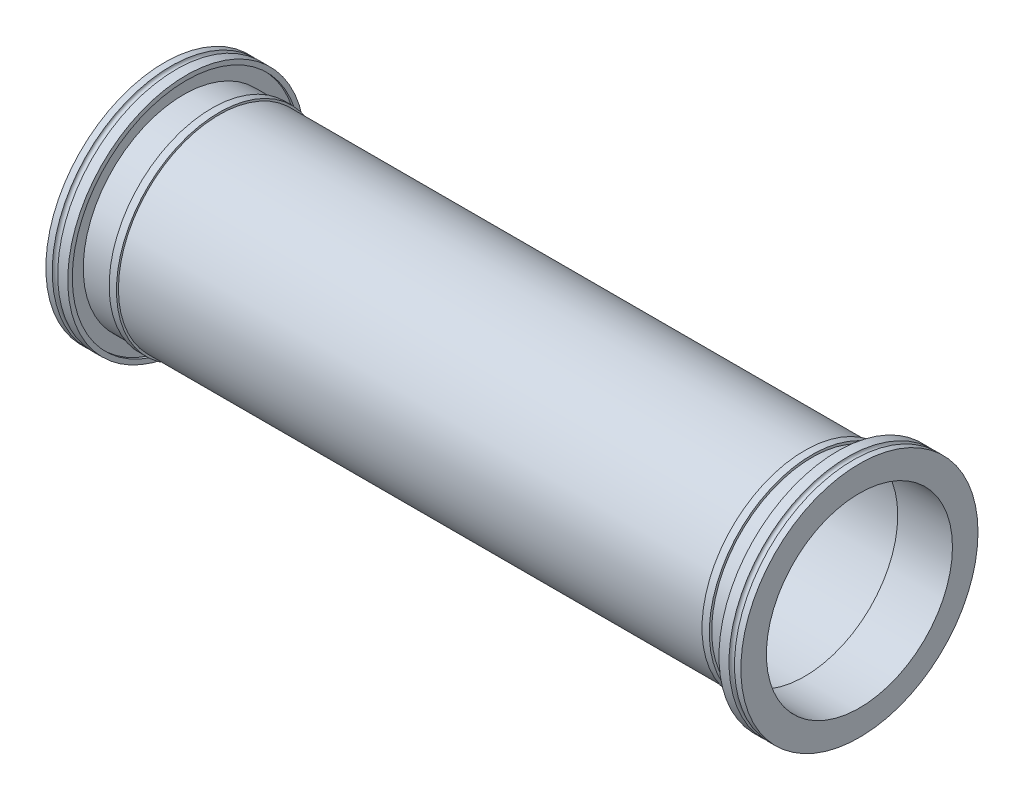
SolidWorks part; units mm, degrees
ref_plane "Front Plane" through (0, 0, 0) normal (0, 0, 1) x (1, 0, 0)
ref_plane "Top Plane" through (0, 0, 0) normal (0, 1, 0) x (1, 0, 0)
ref_plane "Right Plane" through (0, 0, 0) normal (1, 0, 0) x (0, 0, -1)
ref_plane "Plane1" through (0, 0, 0) normal (0, 0, -1) x (-1, 0, 0)
ref_axis "Axis1" through (400.5834, 0, 0) along (-1, 0, 0)
sketch "Sketch1" plane through (0, 0, 0) normal (0, 0, -1) x (-1, 0, 0)
  line L0 (-75.5922, 51.3) -> (-75.5922, 58.3)
  line L1 (-76.7922, 59.5) -> (-77.1922, 59.5)
  line L2 (-78.3922, 58.3) -> (-78.3922, 51.3)
  line L3 (-79.3422, 50.35) -> (-79.6999, 50.35)
  line L4 (-80.6499, 51.3) -> (-80.6499, 58.3)
  line L5 (-81.8499, 59.5) -> (-82.2499, 59.5)
  line L6 (-83.4499, 58.3) -> (-83.4499, 51.3)
  line L7 (-84.3999, 50.35) -> (-84.7577, 50.35)
  line L8 (-85.7077, 51.3) -> (-85.7077, 58.3)
  line L9 (-86.9077, 59.5) -> (-87.3077, 59.5)
  line L10 (-88.5077, 58.3) -> (-88.5077, 51.3)
  line L11 (-89.4577, 50.35) -> (-89.8155, 50.35)
  line L12 (-90.7655, 51.3) -> (-90.7655, 58.3)
  line L13 (-91.9655, 59.5) -> (-92.3655, 59.5)
  line L14 (-93.5655, 58.3) -> (-93.5655, 51.3)
  line L15 (-94.5155, 50.35) -> (-94.8732, 50.35)
  line L16 (-95.8232, 51.3) -> (-95.8232, 58.3)
  line L17 (-97.0232, 59.5) -> (-97.4232, 59.5)
  line L18 (-98.6232, 58.3) -> (-98.6232, 51.3)
  line L19 (-99.5732, 50.35) -> (-99.931, 50.35)
  line L20 (-100.881, 51.3) -> (-100.881, 58.3)
  line L21 (-102.081, 59.5) -> (-102.481, 59.5)
  line L22 (-103.681, 58.3) -> (-103.681, 51.3)
  line L23 (-104.631, 50.35) -> (-104.9888, 50.35)
  line L24 (-105.9388, 51.3) -> (-105.9388, 58.3)
  line L25 (-107.1388, 59.5) -> (-107.5388, 59.5)
  line L26 (-108.7388, 58.3) -> (-108.7388, 51.3)
  line L27 (-109.6888, 50.35) -> (-110.0466, 50.35)
  line L28 (-110.9965, 51.3) -> (-110.9965, 58.3)
  line L29 (-112.1966, 59.5) -> (-112.5966, 59.5)
  line L30 (-113.7965, 58.3) -> (-113.7965, 51.3)
  line L31 (-114.7465, 50.35) -> (-115.1043, 50.35)
  line L32 (-116.0543, 51.3) -> (-116.0543, 58.3)
  line L33 (-117.2543, 59.5) -> (-117.6543, 59.5)
  line L34 (-118.8543, 58.3) -> (-118.8543, 51.3)
  line L35 (-119.8043, 50.35) -> (-120.1621, 50.35)
  line L36 (-121.1121, 51.3) -> (-121.1121, 58.3)
  line L37 (-122.3121, 59.5) -> (-122.7121, 59.5)
  line L38 (-123.9121, 58.3) -> (-123.9121, 51.3)
  line L39 (-124.8621, 50.35) -> (-125.2199, 50.35)
  line L40 (-126.1699, 51.3) -> (-126.1699, 58.3)
  line L41 (-127.3699, 59.5) -> (-127.7699, 59.5)
  line L42 (-128.9699, 58.3) -> (-128.9699, 51.3)
  line L43 (-129.9199, 50.35) -> (-130.2776, 50.35)
  line L44 (-131.2276, 51.3) -> (-131.2276, 58.3)
  line L45 (-132.4276, 59.5) -> (-132.8276, 59.5)
  line L46 (-134.0276, 58.3) -> (-134.0276, 51.3)
  line L47 (-134.9776, 50.35) -> (-135.3354, 50.35)
  line L48 (-136.2854, 51.3) -> (-136.2854, 58.3)
  line L49 (-137.4854, 59.5) -> (-137.8854, 59.5)
  line L50 (-139.0854, 58.3) -> (-139.0854, 51.3)
  line L51 (-140.0354, 50.35) -> (-140.3932, 50.35)
  line L52 (-141.3432, 51.3) -> (-141.3432, 58.3)
  line L53 (-142.5432, 59.5) -> (-142.9432, 59.5)
  line L54 (-144.1432, 58.3) -> (-144.1432, 51.3)
  line L55 (-145.0932, 50.35) -> (-145.4509, 50.35)
  line L56 (-146.4009, 51.3) -> (-146.4009, 58.3)
  line L57 (-147.6009, 59.5) -> (-148.0009, 59.5)
  line L58 (-149.2009, 58.3) -> (-149.2009, 51.3)
  line L59 (-150.1509, 50.35) -> (-150.5087, 50.35)
  line L60 (-151.4587, 51.3) -> (-151.4587, 58.3)
  line L61 (-152.6587, 59.5) -> (-153.0587, 59.5)
  line L62 (-154.2587, 58.3) -> (-154.2587, 51.3)
  line L63 (-155.2087, 50.35) -> (-155.5665, 50.35)
  line L64 (-156.5165, 51.3) -> (-156.5165, 58.3)
  line L65 (-157.7165, 59.5) -> (-158.1165, 59.5)
  line L66 (-159.3165, 58.3) -> (-159.3165, 51.3)
  line L67 (-160.2665, 50.35) -> (-160.6242, 50.35)
  line L68 (-161.5743, 51.3) -> (-161.5743, 58.3)
  line L69 (-162.7742, 59.5) -> (-163.1743, 59.5)
  line L70 (-164.3742, 58.3) -> (-164.3742, 51.3)
  line L71 (-165.3243, 50.35) -> (-165.682, 50.35)
  line L72 (-166.632, 51.3) -> (-166.632, 58.3)
  line L73 (-167.832, 59.5) -> (-168.232, 59.5)
  line L74 (-169.432, 58.3) -> (-169.432, 51.3)
  line L75 (-170.382, 50.35) -> (-170.7398, 50.35)
  line L76 (-171.6898, 51.3) -> (-171.6898, 58.3)
  line L77 (-172.8898, 59.5) -> (-173.2898, 59.5)
  line L78 (-174.4898, 58.3) -> (-174.4898, 51.3)
  line L79 (-175.4398, 50.35) -> (-175.7976, 50.35)
  line L80 (-176.7476, 51.3) -> (-176.7476, 58.3)
  line L81 (-177.9476, 59.5) -> (-178.3476, 59.5)
  line L82 (-179.5476, 58.3) -> (-179.5476, 51.3)
  line L83 (-180.4976, 50.35) -> (-180.8553, 50.35)
  line L84 (-181.8053, 51.3) -> (-181.8053, 58.3)
  line L85 (-183.0053, 59.5) -> (-183.4053, 59.5)
  line L86 (-184.6053, 58.3) -> (-184.6053, 51.3)
  line L87 (-185.5553, 50.35) -> (-185.9131, 50.35)
  line L88 (-186.8631, 51.3) -> (-186.8631, 58.3)
  line L89 (-188.0631, 59.5) -> (-188.4631, 59.5)
  line L90 (-189.6631, 58.3) -> (-189.6631, 51.3)
  line L91 (-190.6131, 50.35) -> (-190.9709, 50.35)
  line L92 (-191.9209, 51.3) -> (-191.9209, 58.3)
  line L93 (-193.1209, 59.5) -> (-193.5209, 59.5)
  line L94 (-194.7209, 58.3) -> (-194.7209, 51.3)
  line L95 (-195.6709, 50.35) -> (-196.0286, 50.35)
  line L96 (-196.9786, 51.3) -> (-196.9786, 58.3)
  line L97 (-198.1786, 59.5) -> (-198.5786, 59.5)
  line L98 (-199.7786, 58.3) -> (-199.7786, 51.3)
  line L99 (-200.7286, 50.35) -> (-201.0864, 50.35)
  line L100 (-202.0364, 51.3) -> (-202.0364, 58.3)
  line L101 (-203.2364, 59.5) -> (-203.6362, 59.5)
  line L102 (-204.8362, 58.3) -> (-204.8362, 51.3)
  line L103 (-205.7862, 50.35) -> (-206.1439, 50.35)
  line L104 (-207.0939, 51.3) -> (-207.0939, 58.3)
  line L105 (-208.2939, 59.5) -> (-208.6942, 59.5)
  line L106 (-209.8942, 58.3) -> (-209.8942, 51.3)
  line L107 (-210.8442, 50.35) -> (-211.2019, 50.35)
  line L108 (-343.6599, 51.3) -> (-343.66, 58.3)
  line L109 (-344.86, 59.5) -> (-345.2599, 59.5)
  line L110 (-346.4599, 58.3) -> (-346.4599, 51.3)
  line L111 (-347.4099, 50.35) -> (-349.1899, 50.35)
  line L112 (-350.5899, 51.75) -> (-350.5899, 55.5)
  line L113 (-351.3899, 56.3) -> (-355.5899, 56.3)
  line L114 (-355.5899, 56.3) -> (-355.5899, 56)
  line L115 (-355.5899, 56) -> (-355.508, 56)
  line L116 (-355.508, 56) -> (-355.508, 55)
  line L117 (-355.508, 55) -> (-371.008, 55)
  line L118 (-371.008, 55) -> (-371.008, 62.5)
  line L119 (-371.008, 62.5) -> (-369.508, 62.5)
  line L120 (-369.508, 62.5) -> (-369.508, 65)
  line L121 (-369.508, 65) -> (-375.008, 65)
  line L122 (-378.008, 65) -> (-381.508, 65)
  line L123 (-381.508, 65) -> (-381.508, 51)
  line L124 (-381.508, 51) -> (-351.508, 51)
  line L125 (-351.508, 51) -> (-351.508, 56)
  line L126 (-351.508, 56) -> (-351.3899, 56)
  line L127 (-350.8899, 55.5) -> (-350.8899, 51.75)
  line L128 (-349.1899, 50.05) -> (-347.5899, 50.05)
  line L129 (-347.5899, 50.05) -> (-347.5899, 50.15)
  line L130 (-347.5899, 50.15) -> (-347.4099, 50.15)
  line L131 (-346.2599, 51.3) -> (-346.26, 58.3)
  line L132 (-345.2599, 59.3) -> (-344.86, 59.3)
  line L133 (-343.86, 58.3) -> (-343.8599, 51.3)
  line L134 (-212.1519, 51.3) -> (-212.1519, 58.3)
  line L135 (-209.6942, 51.3) -> (-209.6942, 58.3)
  line L136 (-208.6942, 59.3) -> (-208.2939, 59.3)
  line L137 (-207.2939, 58.3) -> (-207.2939, 51.3)
  line L138 (-206.1439, 50.15) -> (-205.7862, 50.15)
  line L139 (-204.6362, 51.3) -> (-204.6362, 58.3)
  line L140 (-203.6362, 59.3) -> (-203.2364, 59.3)
  line L141 (-202.2364, 58.3) -> (-202.2364, 51.3)
  line L142 (-201.0864, 50.15) -> (-200.7286, 50.15)
  line L143 (-199.5786, 51.3) -> (-199.5786, 58.3)
  line L144 (-198.5786, 59.3) -> (-198.1786, 59.3)
  line L145 (-197.1786, 58.3) -> (-197.1786, 51.3)
  line L146 (-196.0286, 50.15) -> (-195.6709, 50.15)
  line L147 (-194.5209, 51.3) -> (-194.5209, 58.3)
  line L148 (-193.5209, 59.3) -> (-193.1209, 59.3)
  line L149 (-192.1209, 58.3) -> (-192.1209, 51.3)
  line L150 (-190.9709, 50.15) -> (-190.6131, 50.15)
  line L151 (-189.4631, 51.3) -> (-189.4631, 58.3)
  line L152 (-188.4631, 59.3) -> (-188.0631, 59.3)
  line L153 (-187.0631, 58.3) -> (-187.0631, 51.3)
  line L154 (-185.9131, 50.15) -> (-185.5553, 50.15)
  line L155 (-184.4053, 51.3) -> (-184.4053, 58.3)
  line L156 (-183.4053, 59.3) -> (-183.0053, 59.3)
  line L157 (-182.0053, 58.3) -> (-182.0053, 51.3)
  line L158 (-180.8553, 50.15) -> (-180.4976, 50.15)
  line L159 (-179.3476, 51.3) -> (-179.3476, 58.3)
  line L160 (-178.3476, 59.3) -> (-177.9476, 59.3)
  line L161 (-176.9476, 58.3) -> (-176.9476, 51.3)
  line L162 (-175.7976, 50.15) -> (-175.4398, 50.15)
  line L163 (-174.2898, 51.3) -> (-174.2898, 58.3)
  line L164 (-173.2898, 59.3) -> (-172.8898, 59.3)
  line L165 (-171.8898, 58.3) -> (-171.8898, 51.3)
  line L166 (-170.7398, 50.15) -> (-170.382, 50.15)
  line L167 (-169.232, 51.3) -> (-169.232, 58.3)
  line L168 (-168.232, 59.3) -> (-167.832, 59.3)
  line L169 (-166.832, 58.3) -> (-166.832, 51.3)
  line L170 (-165.682, 50.15) -> (-165.3243, 50.15)
  line L171 (-164.1743, 51.3) -> (-164.1743, 58.3)
  line L172 (-163.1743, 59.3) -> (-162.7742, 59.3)
  line L173 (-161.7742, 58.3) -> (-161.7742, 51.3)
  line L174 (-160.6242, 50.15) -> (-160.2665, 50.15)
  line L175 (-159.1165, 51.3) -> (-159.1165, 58.3)
  line L176 (-158.1165, 59.3) -> (-157.7165, 59.3)
  line L177 (-156.7165, 58.3) -> (-156.7165, 51.3)
  line L178 (-155.5665, 50.15) -> (-155.2087, 50.15)
  line L179 (-154.0587, 51.3) -> (-154.0587, 58.3)
  line L180 (-153.0587, 59.3) -> (-152.6587, 59.3)
  line L181 (-151.6587, 58.3) -> (-151.6587, 51.3)
  line L182 (-150.5087, 50.15) -> (-150.1509, 50.15)
  line L183 (-149.0009, 51.3) -> (-149.0009, 58.3)
  line L184 (-148.0009, 59.3) -> (-147.6009, 59.3)
  line L185 (-146.6009, 58.3) -> (-146.6009, 51.3)
  line L186 (-145.4509, 50.15) -> (-145.0932, 50.15)
  line L187 (-143.9432, 51.3) -> (-143.9432, 58.3)
  line L188 (-142.9432, 59.3) -> (-142.5432, 59.3)
  line L189 (-141.5432, 58.3) -> (-141.5432, 51.3)
  line L190 (-140.3932, 50.15) -> (-140.0354, 50.15)
  line L191 (-138.8854, 51.3) -> (-138.8854, 58.3)
  line L192 (-137.8854, 59.3) -> (-137.4854, 59.3)
  line L193 (-136.4854, 58.3) -> (-136.4854, 51.3)
  line L194 (-135.3354, 50.15) -> (-134.9776, 50.15)
  line L195 (-133.8276, 51.3) -> (-133.8276, 58.3)
  line L196 (-132.8276, 59.3) -> (-132.4276, 59.3)
  line L197 (-131.4276, 58.3) -> (-131.4276, 51.3)
  line L198 (-130.2776, 50.15) -> (-129.9199, 50.15)
  line L199 (-128.7699, 51.3) -> (-128.7699, 58.3)
  line L200 (-127.7699, 59.3) -> (-127.3699, 59.3)
  line L201 (-126.3699, 58.3) -> (-126.3699, 51.3)
  line L202 (-125.2199, 50.15) -> (-124.8621, 50.15)
  line L203 (-123.7121, 51.3) -> (-123.7121, 58.3)
  line L204 (-122.7121, 59.3) -> (-122.3121, 59.3)
  line L205 (-121.3121, 58.3) -> (-121.3121, 51.3)
  line L206 (-120.1621, 50.15) -> (-119.8043, 50.15)
  line L207 (-118.6543, 51.3) -> (-118.6543, 58.3)
  line L208 (-117.6543, 59.3) -> (-117.2543, 59.3)
  line L209 (-116.2543, 58.3) -> (-116.2543, 51.3)
  line L210 (-115.1043, 50.15) -> (-114.7465, 50.15)
  line L211 (-113.5966, 51.3) -> (-113.5966, 58.3)
  line L212 (-112.5966, 59.3) -> (-112.1966, 59.3)
  line L213 (-111.1966, 58.3) -> (-111.1966, 51.3)
  line L214 (-110.0466, 50.15) -> (-109.6888, 50.15)
  line L215 (-108.5388, 51.3) -> (-108.5388, 58.3)
  line L216 (-107.5388, 59.3) -> (-107.1388, 59.3)
  line L217 (-106.1388, 58.3) -> (-106.1388, 51.3)
  line L218 (-104.9888, 50.15) -> (-104.631, 50.15)
  line L219 (-103.481, 51.3) -> (-103.481, 58.3)
  line L220 (-102.481, 59.3) -> (-102.081, 59.3)
  line L221 (-101.081, 58.3) -> (-101.081, 51.3)
  line L222 (-99.931, 50.15) -> (-99.5732, 50.15)
  line L223 (-98.4232, 51.3) -> (-98.4232, 58.3)
  line L224 (-97.4232, 59.3) -> (-97.0232, 59.3)
  line L225 (-96.0232, 58.3) -> (-96.0232, 51.3)
  line L226 (-94.8732, 50.15) -> (-94.5155, 50.15)
  line L227 (-93.3655, 51.3) -> (-93.3655, 58.3)
  line L228 (-92.3655, 59.3) -> (-91.9655, 59.3)
  line L229 (-90.9655, 58.3) -> (-90.9655, 51.3)
  line L230 (-89.8155, 50.15) -> (-89.4577, 50.15)
  line L231 (-88.3077, 51.3) -> (-88.3077, 58.3)
  line L232 (-87.3077, 59.3) -> (-86.9077, 59.3)
  line L233 (-85.9077, 58.3) -> (-85.9077, 51.3)
  line L234 (-84.7577, 50.15) -> (-84.3999, 50.15)
  line L235 (-83.2499, 51.3) -> (-83.2499, 58.3)
  line L236 (-82.2499, 59.3) -> (-81.8499, 59.3)
  line L237 (-80.8499, 58.3) -> (-80.8499, 51.3)
  line L238 (-79.6999, 50.15) -> (-79.3422, 50.15)
  line L239 (-78.1922, 51.3) -> (-78.1922, 58.3)
  line L240 (-77.1922, 59.3) -> (-76.7922, 59.3)
  line L241 (-75.7922, 58.3) -> (-75.7922, 51.3)
  line L242 (-74.6422, 50.15) -> (-74.2844, 50.15)
  line L243 (-73.1344, 51.3) -> (-73.1344, 58.3)
  line L244 (-72.1344, 59.3) -> (-71.7344, 59.3)
  line L245 (-70.7344, 58.3) -> (-70.7344, 51.3)
  line L246 (-69.5844, 50.15) -> (-69.2266, 50.15)
  line L247 (-68.0766, 51.3) -> (-68.0766, 58.3)
  line L248 (-67.0766, 59.3) -> (-66.6766, 59.3)
  line L249 (-65.6766, 58.3) -> (-65.6766, 51.3)
  line L250 (-64.5266, 50.15) -> (-64.1689, 50.15)
  line L251 (-63.0189, 51.3) -> (-63.0189, 58.3)
  line L252 (-62.0189, 59.3) -> (-61.6189, 59.3)
  line L253 (-60.6189, 58.3) -> (-60.6189, 51.3)
  line L254 (-59.4688, 50.15) -> (-59.1111, 50.15)
  line L255 (-57.9611, 51.3) -> (-57.9611, 58.3)
  line L256 (-56.9611, 59.3) -> (-56.5611, 59.3)
  line L257 (-55.5611, 58.3) -> (-55.5611, 51.3)
  line L258 (-54.4111, 50.15) -> (-54.0533, 50.15)
  line L259 (-52.9033, 51.3) -> (-52.9033, 58.3)
  line L260 (-51.9033, 59.3) -> (-51.5033, 59.3)
  line L261 (-50.5033, 58.3) -> (-50.5033, 51.3)
  line L262 (-49.3533, 50.15) -> (-48.9955, 50.15)
  line L263 (-47.8455, 51.3) -> (-47.8455, 58.3)
  line L264 (-46.8455, 59.3) -> (-46.4455, 59.3)
  line L265 (-45.4455, 58.3) -> (-45.4455, 51.3)
  line L266 (-44.2955, 50.15) -> (-43.9378, 50.15)
  line L267 (-42.7878, 51.3) -> (-42.7878, 58.3)
  line L268 (-41.7878, 59.3) -> (-41.3878, 59.3)
  line L269 (-40.3878, 58.3) -> (-40.3878, 51.3)
  line L270 (-39.2378, 50.15) -> (-38.88, 50.15)
  line L271 (-37.73, 51.3) -> (-37.73, 58.3)
  line L272 (-36.73, 59.3) -> (-36.33, 59.3)
  line L273 (-35.33, 58.3) -> (-35.33, 51.3)
  line L274 (-34.18, 50.15) -> (-34, 50.15)
  line L275 (-34, 50.15) -> (-34, 50.05)
  line L276 (-34, 50.05) -> (-32.4, 50.05)
  line L277 (-30.7, 51.75) -> (-30.7, 55.5)
  line L278 (-30.2, 56) -> (-30, 56)
  line L279 (-30, 56) -> (-30, 51)
  line L280 (-30, 51) -> (0, 51)
  line L281 (0, 51) -> (0, 65)
  line L282 (0, 65) -> (-3.5, 65)
  line L283 (-6.5, 65) -> (-12, 65)
  line L284 (-12, 65) -> (-12, 62.5)
  line L285 (-12, 62.5) -> (-10.5, 62.5)
  line L286 (-10.5, 62.5) -> (-10.5, 55)
  line L287 (-10.5, 55) -> (-26, 55)
  line L288 (-26, 55) -> (-26, 56.3)
  line L289 (-26, 56.3) -> (-30.2, 56.3)
  line L290 (-31, 55.5) -> (-31, 51.75)
  line L291 (-32.4, 50.35) -> (-34.18, 50.35)
  line L292 (-35.13, 51.3) -> (-35.13, 58.3)
  line L293 (-36.33, 59.5) -> (-36.73, 59.5)
  line L294 (-37.93, 58.3) -> (-37.93, 51.3)
  line L295 (-38.88, 50.35) -> (-39.2378, 50.35)
  line L296 (-40.1878, 51.3) -> (-40.1878, 58.3)
  line L297 (-41.3878, 59.5) -> (-41.7878, 59.5)
  line L298 (-42.9878, 58.3) -> (-42.9878, 51.3)
  line L299 (-43.9378, 50.35) -> (-44.2955, 50.35)
  line L300 (-45.2455, 51.3) -> (-45.2455, 58.3)
  line L301 (-46.4455, 59.5) -> (-46.8455, 59.5)
  line L302 (-48.0455, 58.3) -> (-48.0455, 51.3)
  line L303 (-48.9955, 50.35) -> (-49.3533, 50.35)
  line L304 (-50.3033, 51.3) -> (-50.3033, 58.3)
  line L305 (-51.5033, 59.5) -> (-51.9033, 59.5)
  line L306 (-53.1033, 58.3) -> (-53.1033, 51.3)
  line L307 (-54.0533, 50.35) -> (-54.4111, 50.35)
  line L308 (-55.3611, 51.3) -> (-55.3611, 58.3)
  line L309 (-56.5611, 59.5) -> (-56.9611, 59.5)
  line L310 (-58.1611, 58.3) -> (-58.1611, 51.3)
  line L311 (-59.1111, 50.35) -> (-59.4688, 50.35)
  line L312 (-60.4188, 51.3) -> (-60.4189, 58.3)
  line L313 (-61.6189, 59.5) -> (-62.0189, 59.5)
  line L314 (-63.2188, 58.3) -> (-63.2188, 51.3)
  line L315 (-64.1689, 50.35) -> (-64.5266, 50.35)
  line L316 (-65.4766, 51.3) -> (-65.4766, 58.3)
  line L317 (-66.6766, 59.5) -> (-67.0766, 59.5)
  line L318 (-68.2766, 58.3) -> (-68.2766, 51.3)
  line L319 (-69.2266, 50.35) -> (-69.5844, 50.35)
  line L320 (-70.5344, 51.3) -> (-70.5344, 58.3)
  line L321 (-71.7344, 59.5) -> (-72.1344, 59.5)
  line L322 (-73.3344, 58.3) -> (-73.3344, 51.3)
  line L323 (-74.2844, 50.35) -> (-74.6422, 50.35)
  line L324 (-250, 0) -> (0, 0) construction
  line L325 (-213.3519, 59.5) -> (-213.7522, 59.5)
  line L326 (-214.9522, 58.3) -> (-214.9522, 51.3)
  line L327 (-214.7522, 51.3) -> (-214.7522, 58.3)
  line L328 (-213.7522, 59.3) -> (-213.3519, 59.3)
  line L329 (-212.3519, 58.3) -> (-212.3519, 51.3)
  line L330 (-211.2019, 50.15) -> (-210.8442, 50.15)
  line L331 (-215.9022, 50.35) -> (-216.2599, 50.35)
  line L332 (-217.2099, 51.3) -> (-217.2099, 58.3)
  line L333 (-218.4099, 59.5) -> (-218.8102, 59.5)
  line L334 (-220.0102, 58.3) -> (-220.0102, 51.3)
  line L335 (-219.8102, 51.3) -> (-219.8102, 58.3)
  line L336 (-218.8102, 59.3) -> (-218.4099, 59.3)
  line L337 (-217.4099, 58.3) -> (-217.4099, 51.3)
  line L338 (-216.2599, 50.15) -> (-215.9022, 50.15)
  line L339 (-220.9602, 50.35) -> (-221.3179, 50.35)
  line L340 (-222.2679, 51.3) -> (-222.2679, 58.3)
  line L341 (-223.4679, 59.5) -> (-223.8682, 59.5)
  line L342 (-225.0682, 58.3) -> (-225.0682, 51.3)
  line L343 (-224.8682, 51.3) -> (-224.8682, 58.3)
  line L344 (-223.8682, 59.3) -> (-223.4679, 59.3)
  line L345 (-222.4679, 58.3) -> (-222.4679, 51.3)
  line L346 (-221.3179, 50.15) -> (-220.9602, 50.15)
  line L347 (-226.0182, 50.35) -> (-226.3759, 50.35)
  line L348 (-227.3259, 51.3) -> (-227.3259, 58.3)
  line L349 (-228.5259, 59.5) -> (-228.9262, 59.5)
  line L350 (-230.1262, 58.3) -> (-230.1262, 51.3)
  line L351 (-229.9262, 51.3) -> (-229.9262, 58.3)
  line L352 (-228.9262, 59.3) -> (-228.5259, 59.3)
  line L353 (-227.5259, 58.3) -> (-227.5259, 51.3)
  line L354 (-226.3759, 50.15) -> (-226.0182, 50.15)
  line L355 (-231.0762, 50.35) -> (-231.4339, 50.35)
  line L356 (-232.3839, 51.3) -> (-232.3839, 58.3)
  line L357 (-233.5839, 59.5) -> (-233.9842, 59.5)
  line L358 (-235.1842, 58.3) -> (-235.1842, 51.3)
  line L359 (-234.9842, 51.3) -> (-234.9842, 58.3)
  line L360 (-233.9842, 59.3) -> (-233.5839, 59.3)
  line L361 (-232.5839, 58.3) -> (-232.5839, 51.3)
  line L362 (-231.4339, 50.15) -> (-231.0762, 50.15)
  line L363 (-236.1342, 50.35) -> (-236.4919, 50.35)
  line L364 (-237.4419, 51.3) -> (-237.4419, 58.3)
  line L365 (-238.6419, 59.5) -> (-239.0422, 59.5)
  line L366 (-240.2422, 58.3) -> (-240.2422, 51.3)
  line L367 (-240.0422, 51.3) -> (-240.0422, 58.3)
  line L368 (-239.0422, 59.3) -> (-238.6419, 59.3)
  line L369 (-237.6419, 58.3) -> (-237.6419, 51.3)
  line L370 (-236.4919, 50.15) -> (-236.1342, 50.15)
  line L371 (-241.1922, 50.35) -> (-241.5499, 50.35)
  line L372 (-242.4999, 51.3) -> (-242.4999, 58.3)
  line L373 (-243.6999, 59.5) -> (-244.1002, 59.5)
  line L374 (-245.3002, 58.3) -> (-245.3002, 51.3)
  line L375 (-245.1002, 51.3) -> (-245.1002, 58.3)
  line L376 (-244.1002, 59.3) -> (-243.6999, 59.3)
  line L377 (-242.6999, 58.3) -> (-242.6999, 51.3)
  line L378 (-241.5499, 50.15) -> (-241.1922, 50.15)
  line L379 (-246.2502, 50.35) -> (-246.6079, 50.35)
  line L380 (-247.5579, 51.3) -> (-247.5579, 58.3)
  line L381 (-248.7579, 59.5) -> (-249.1582, 59.5)
  line L382 (-250.3582, 58.3) -> (-250.3582, 51.3)
  line L383 (-250.1582, 51.3) -> (-250.1582, 58.3)
  line L384 (-249.1582, 59.3) -> (-248.7579, 59.3)
  line L385 (-247.7579, 58.3) -> (-247.7579, 51.3)
  line L386 (-246.6079, 50.15) -> (-246.2502, 50.15)
  line L387 (-251.3082, 50.35) -> (-251.6659, 50.35)
  line L388 (-252.6159, 51.3) -> (-252.6159, 58.3)
  line L389 (-253.8159, 59.5) -> (-254.2162, 59.5)
  line L390 (-255.4162, 58.3) -> (-255.4162, 51.3)
  line L391 (-255.2162, 51.3) -> (-255.2162, 58.3)
  line L392 (-254.2162, 59.3) -> (-253.8159, 59.3)
  line L393 (-252.8159, 58.3) -> (-252.8159, 51.3)
  line L394 (-251.6659, 50.15) -> (-251.3082, 50.15)
  line L395 (-256.3662, 50.35) -> (-256.7239, 50.35)
  line L396 (-257.6739, 51.3) -> (-257.6739, 58.3)
  line L397 (-258.8739, 59.5) -> (-259.2742, 59.5)
  line L398 (-260.4742, 58.3) -> (-260.4742, 51.3)
  line L399 (-260.2742, 51.3) -> (-260.2742, 58.3)
  line L400 (-259.2742, 59.3) -> (-258.8739, 59.3)
  line L401 (-257.8739, 58.3) -> (-257.8739, 51.3)
  line L402 (-256.7239, 50.15) -> (-256.3662, 50.15)
  line L403 (-261.4242, 50.35) -> (-261.7819, 50.35)
  line L404 (-262.7319, 51.3) -> (-262.7319, 58.3)
  line L405 (-263.9319, 59.5) -> (-264.3322, 59.5)
  line L406 (-265.5322, 58.3) -> (-265.5322, 51.3)
  line L407 (-265.3322, 51.3) -> (-265.3322, 58.3)
  line L408 (-264.3322, 59.3) -> (-263.9319, 59.3)
  line L409 (-262.9319, 58.3) -> (-262.9319, 51.3)
  line L410 (-261.7819, 50.15) -> (-261.4242, 50.15)
  line L411 (-266.4822, 50.35) -> (-266.8399, 50.35)
  line L412 (-267.7899, 51.3) -> (-267.7899, 58.3)
  line L413 (-268.9899, 59.5) -> (-269.3902, 59.5)
  line L414 (-270.5902, 58.3) -> (-270.5902, 51.3)
  line L415 (-270.3902, 51.3) -> (-270.3902, 58.3)
  line L416 (-269.3902, 59.3) -> (-268.9899, 59.3)
  line L417 (-267.9899, 58.3) -> (-267.9899, 51.3)
  line L418 (-266.8399, 50.15) -> (-266.4822, 50.15)
  line L419 (-271.5402, 50.35) -> (-271.8979, 50.35)
  line L420 (-272.8479, 51.3) -> (-272.8479, 58.3)
  line L421 (-274.0479, 59.5) -> (-274.4482, 59.5)
  line L422 (-275.6482, 58.3) -> (-275.6482, 51.3)
  line L423 (-275.4482, 51.3) -> (-275.4482, 58.3)
  line L424 (-274.4482, 59.3) -> (-274.0479, 59.3)
  line L425 (-273.0479, 58.3) -> (-273.0479, 51.3)
  line L426 (-271.8979, 50.15) -> (-271.5402, 50.15)
  line L427 (-276.5982, 50.35) -> (-276.9559, 50.35)
  line L428 (-277.9059, 51.3) -> (-277.9059, 58.3)
  line L429 (-279.1059, 59.5) -> (-279.5062, 59.5)
  line L430 (-280.7062, 58.3) -> (-280.7062, 51.3)
  line L431 (-280.5062, 51.3) -> (-280.5062, 58.3)
  line L432 (-279.5062, 59.3) -> (-279.1059, 59.3)
  line L433 (-278.1059, 58.3) -> (-278.1059, 51.3)
  line L434 (-276.9559, 50.15) -> (-276.5982, 50.15)
  line L435 (-281.6562, 50.35) -> (-282.0139, 50.35)
  line L436 (-282.9639, 51.3) -> (-282.9639, 58.3)
  line L437 (-284.1639, 59.5) -> (-284.5642, 59.5)
  line L438 (-285.7642, 58.3) -> (-285.7642, 51.3)
  line L439 (-285.5642, 51.3) -> (-285.5642, 58.3)
  line L440 (-284.5642, 59.3) -> (-284.1639, 59.3)
  line L441 (-283.1639, 58.3) -> (-283.1639, 51.3)
  line L442 (-282.0139, 50.15) -> (-281.6562, 50.15)
  line L443 (-286.7142, 50.35) -> (-287.0719, 50.35)
  line L444 (-288.0219, 51.3) -> (-288.0219, 58.3)
  line L445 (-289.2219, 59.5) -> (-289.6222, 59.5)
  line L446 (-290.8222, 58.3) -> (-290.8222, 51.3)
  line L447 (-290.6222, 51.3) -> (-290.6222, 58.3)
  line L448 (-289.6222, 59.3) -> (-289.2219, 59.3)
  line L449 (-288.2219, 58.3) -> (-288.2219, 51.3)
  line L450 (-287.0719, 50.15) -> (-286.7142, 50.15)
  line L451 (-291.7722, 50.35) -> (-292.1299, 50.35)
  line L452 (-293.0799, 51.3) -> (-293.0799, 58.3)
  line L453 (-294.2799, 59.5) -> (-294.6802, 59.5)
  line L454 (-295.8802, 58.3) -> (-295.8802, 51.3)
  line L455 (-295.6802, 51.3) -> (-295.6802, 58.3)
  line L456 (-294.6802, 59.3) -> (-294.2799, 59.3)
  line L457 (-293.2799, 58.3) -> (-293.2799, 51.3)
  line L458 (-292.1299, 50.15) -> (-291.7722, 50.15)
  line L459 (-296.8302, 50.35) -> (-297.1879, 50.35)
  line L460 (-298.1379, 51.3) -> (-298.1379, 58.3)
  line L461 (-299.3379, 59.5) -> (-299.7382, 59.5)
  line L462 (-300.9382, 58.3) -> (-300.9382, 51.3)
  line L463 (-300.7382, 51.3) -> (-300.7382, 58.3)
  line L464 (-299.7382, 59.3) -> (-299.3379, 59.3)
  line L465 (-298.3379, 58.3) -> (-298.3379, 51.3)
  line L466 (-297.1879, 50.15) -> (-296.8302, 50.15)
  line L467 (-301.8882, 50.35) -> (-302.2459, 50.35)
  line L468 (-303.1959, 51.3) -> (-303.1959, 58.3)
  line L469 (-304.3959, 59.5) -> (-304.7962, 59.5)
  line L470 (-305.9962, 58.3) -> (-305.9962, 51.3)
  line L471 (-305.7962, 51.3) -> (-305.7962, 58.3)
  line L472 (-304.7962, 59.3) -> (-304.3959, 59.3)
  line L473 (-303.3959, 58.3) -> (-303.3959, 51.3)
  line L474 (-302.2459, 50.15) -> (-301.8882, 50.15)
  line L475 (-306.9462, 50.35) -> (-307.3039, 50.35)
  line L476 (-308.2539, 51.3) -> (-308.2539, 58.3)
  line L477 (-309.4539, 59.5) -> (-309.8542, 59.5)
  line L478 (-311.0542, 58.3) -> (-311.0542, 51.3)
  line L479 (-310.8542, 51.3) -> (-310.8542, 58.3)
  line L480 (-309.8542, 59.3) -> (-309.4539, 59.3)
  line L481 (-308.4539, 58.3) -> (-308.4539, 51.3)
  line L482 (-307.3039, 50.15) -> (-306.9462, 50.15)
  line L483 (-312.0042, 50.35) -> (-312.3619, 50.35)
  line L484 (-313.3119, 51.3) -> (-313.3119, 58.3)
  line L485 (-314.5119, 59.5) -> (-314.9122, 59.5)
  line L486 (-316.1122, 58.3) -> (-316.1122, 51.3)
  line L487 (-315.9122, 51.3) -> (-315.9122, 58.3)
  line L488 (-314.9122, 59.3) -> (-314.5119, 59.3)
  line L489 (-313.5119, 58.3) -> (-313.5119, 51.3)
  line L490 (-312.3619, 50.15) -> (-312.0042, 50.15)
  line L491 (-317.0622, 50.35) -> (-317.4199, 50.35)
  line L492 (-318.3699, 51.3) -> (-318.3699, 58.3)
  line L493 (-319.5699, 59.5) -> (-319.9702, 59.5)
  line L494 (-321.1702, 58.3) -> (-321.1702, 51.3)
  line L495 (-320.9702, 51.3) -> (-320.9702, 58.3)
  line L496 (-319.9702, 59.3) -> (-319.5699, 59.3)
  line L497 (-318.5699, 58.3) -> (-318.5699, 51.3)
  line L498 (-317.4199, 50.15) -> (-317.0622, 50.15)
  line L499 (-322.1202, 50.35) -> (-322.4779, 50.35)
  line L500 (-323.4279, 51.3) -> (-323.4279, 58.3)
  line L501 (-324.6279, 59.5) -> (-325.0282, 59.5)
  line L502 (-326.2282, 58.3) -> (-326.2282, 51.3)
  line L503 (-326.0282, 51.3) -> (-326.0282, 58.3)
  line L504 (-325.0282, 59.3) -> (-324.6279, 59.3)
  line L505 (-323.6279, 58.3) -> (-323.6279, 51.3)
  line L506 (-322.4779, 50.15) -> (-322.1202, 50.15)
  line L507 (-327.1782, 50.35) -> (-327.5359, 50.35)
  line L508 (-328.4859, 51.3) -> (-328.4859, 58.3)
  line L509 (-329.6859, 59.5) -> (-330.0862, 59.5)
  line L510 (-331.2862, 58.3) -> (-331.2862, 51.3)
  line L511 (-331.0862, 51.3) -> (-331.0862, 58.3)
  line L512 (-330.0862, 59.3) -> (-329.6859, 59.3)
  line L513 (-328.6859, 58.3) -> (-328.6859, 51.3)
  line L514 (-327.5359, 50.15) -> (-327.1782, 50.15)
  line L515 (-332.2362, 50.35) -> (-332.5939, 50.35)
  line L516 (-333.5439, 51.3) -> (-333.5439, 58.3)
  line L517 (-334.7439, 59.5) -> (-335.1442, 59.5)
  line L518 (-336.3442, 58.3) -> (-336.3442, 51.3)
  line L519 (-336.1442, 51.3) -> (-336.1442, 58.3)
  line L520 (-335.1442, 59.3) -> (-334.7439, 59.3)
  line L521 (-333.7439, 58.3) -> (-333.7439, 51.3)
  line L522 (-332.5939, 50.15) -> (-332.2362, 50.15)
  line L523 (-337.2942, 50.35) -> (-337.6519, 50.35)
  line L524 (-338.6019, 51.3) -> (-338.6019, 58.3)
  line L525 (-339.8019, 59.5) -> (-340.2022, 59.5)
  line L526 (-341.4022, 58.3) -> (-341.4022, 51.3)
  line L527 (-341.2022, 51.3) -> (-341.2022, 58.3)
  line L528 (-340.2022, 59.3) -> (-339.8019, 59.3)
  line L529 (-338.8019, 58.3) -> (-338.8019, 51.3)
  line L530 (-337.6519, 50.15) -> (-337.2942, 50.15)
  line L531 (-205.7862, 50.35) -> (-210.8442, 50.35) construction
  line L532 (-342.3522, 50.35) -> (-342.7099, 50.35)
  line L533 (-342.3522, 50.15) -> (-342.7099, 50.15)
  arc A0 (-75.5922, 58.3) -> (-76.7922, 59.5) centre (-76.7922, 58.3) ccw
  arc A1 (-77.1922, 59.5) -> (-78.3922, 58.3) centre (-77.1922, 58.3) ccw
  arc A2 (-78.3922, 51.3) -> (-79.3422, 50.35) centre (-79.3422, 51.3) cw
  arc A3 (-79.6999, 50.35) -> (-80.6499, 51.3) centre (-79.6999, 51.3) cw
  arc A4 (-80.6499, 58.3) -> (-81.8499, 59.5) centre (-81.8499, 58.3) ccw
  arc A5 (-82.2499, 59.5) -> (-83.4499, 58.3) centre (-82.2499, 58.3) ccw
  arc A6 (-83.4499, 51.3) -> (-84.3999, 50.35) centre (-84.3999, 51.3) cw
  arc A7 (-84.7577, 50.35) -> (-85.7077, 51.3) centre (-84.7577, 51.3) cw
  arc A8 (-85.7077, 58.3) -> (-86.9077, 59.5) centre (-86.9077, 58.3) ccw
  arc A9 (-87.3077, 59.5) -> (-88.5077, 58.3) centre (-87.3077, 58.3) ccw
  arc A10 (-88.5077, 51.3) -> (-89.4577, 50.35) centre (-89.4577, 51.3) cw
  arc A11 (-89.8155, 50.35) -> (-90.7655, 51.3) centre (-89.8155, 51.3) cw
  arc A12 (-90.7655, 58.3) -> (-91.9655, 59.5) centre (-91.9655, 58.3) ccw
  arc A13 (-92.3655, 59.5) -> (-93.5655, 58.3) centre (-92.3655, 58.3) ccw
  arc A14 (-93.5655, 51.3) -> (-94.5155, 50.35) centre (-94.5155, 51.3) cw
  arc A15 (-94.8732, 50.35) -> (-95.8232, 51.3) centre (-94.8732, 51.3) cw
  arc A16 (-95.8232, 58.3) -> (-97.0232, 59.5) centre (-97.0232, 58.3) ccw
  arc A17 (-97.4232, 59.5) -> (-98.6232, 58.3) centre (-97.4232, 58.3) ccw
  arc A18 (-98.6232, 51.3) -> (-99.5732, 50.35) centre (-99.5732, 51.3) cw
  arc A19 (-99.931, 50.35) -> (-100.881, 51.3) centre (-99.931, 51.3) cw
  arc A20 (-100.881, 58.3) -> (-102.081, 59.5) centre (-102.081, 58.3) ccw
  arc A21 (-102.481, 59.5) -> (-103.681, 58.3) centre (-102.481, 58.3) ccw
  arc A22 (-103.681, 51.3) -> (-104.631, 50.35) centre (-104.631, 51.3) cw
  arc A23 (-104.9888, 50.35) -> (-105.9388, 51.3) centre (-104.9888, 51.3) cw
  arc A24 (-105.9388, 58.3) -> (-107.1388, 59.5) centre (-107.1388, 58.3) ccw
  arc A25 (-107.5388, 59.5) -> (-108.7388, 58.3) centre (-107.5388, 58.3) ccw
  arc A26 (-108.7388, 51.3) -> (-109.6888, 50.35) centre (-109.6888, 51.3) cw
  arc A27 (-110.0466, 50.35) -> (-110.9965, 51.3) centre (-110.0466, 51.3) cw
  arc A28 (-110.9965, 58.3) -> (-112.1966, 59.5) centre (-112.1966, 58.3) ccw
  arc A29 (-112.5966, 59.5) -> (-113.7965, 58.3) centre (-112.5966, 58.3) ccw
  arc A30 (-113.7965, 51.3) -> (-114.7465, 50.35) centre (-114.7465, 51.3) cw
  arc A31 (-115.1043, 50.35) -> (-116.0543, 51.3) centre (-115.1043, 51.3) cw
  arc A32 (-116.0543, 58.3) -> (-117.2543, 59.5) centre (-117.2543, 58.3) ccw
  arc A33 (-117.6543, 59.5) -> (-118.8543, 58.3) centre (-117.6543, 58.3) ccw
  arc A34 (-118.8543, 51.3) -> (-119.8043, 50.35) centre (-119.8043, 51.3) cw
  arc A35 (-120.1621, 50.35) -> (-121.1121, 51.3) centre (-120.1621, 51.3) cw
  arc A36 (-121.1121, 58.3) -> (-122.3121, 59.5) centre (-122.3121, 58.3) ccw
  arc A37 (-122.7121, 59.5) -> (-123.9121, 58.3) centre (-122.7121, 58.3) ccw
  arc A38 (-123.9121, 51.3) -> (-124.8621, 50.35) centre (-124.8621, 51.3) cw
  arc A39 (-125.2199, 50.35) -> (-126.1699, 51.3) centre (-125.2199, 51.3) cw
  arc A40 (-126.1699, 58.3) -> (-127.3699, 59.5) centre (-127.3699, 58.3) ccw
  arc A41 (-127.7699, 59.5) -> (-128.9699, 58.3) centre (-127.7699, 58.3) ccw
  arc A42 (-128.9699, 51.3) -> (-129.9199, 50.35) centre (-129.9199, 51.3) cw
  arc A43 (-130.2776, 50.35) -> (-131.2276, 51.3) centre (-130.2776, 51.3) cw
  arc A44 (-131.2276, 58.3) -> (-132.4276, 59.5) centre (-132.4276, 58.3) ccw
  arc A45 (-132.8276, 59.5) -> (-134.0276, 58.3) centre (-132.8276, 58.3) ccw
  arc A46 (-134.0276, 51.3) -> (-134.9776, 50.35) centre (-134.9776, 51.3) cw
  arc A47 (-135.3354, 50.35) -> (-136.2854, 51.3) centre (-135.3354, 51.3) cw
  arc A48 (-136.2854, 58.3) -> (-137.4854, 59.5) centre (-137.4854, 58.3) ccw
  arc A49 (-137.8854, 59.5) -> (-139.0854, 58.3) centre (-137.8854, 58.3) ccw
  arc A50 (-139.0854, 51.3) -> (-140.0354, 50.35) centre (-140.0354, 51.3) cw
  arc A51 (-140.3932, 50.35) -> (-141.3432, 51.3) centre (-140.3932, 51.3) cw
  arc A52 (-141.3432, 58.3) -> (-142.5432, 59.5) centre (-142.5432, 58.3) ccw
  arc A53 (-142.9432, 59.5) -> (-144.1432, 58.3) centre (-142.9432, 58.3) ccw
  arc A54 (-144.1432, 51.3) -> (-145.0932, 50.35) centre (-145.0932, 51.3) cw
  arc A55 (-145.4509, 50.35) -> (-146.4009, 51.3) centre (-145.4509, 51.3) cw
  arc A56 (-146.4009, 58.3) -> (-147.6009, 59.5) centre (-147.6009, 58.3) ccw
  arc A57 (-148.0009, 59.5) -> (-149.2009, 58.3) centre (-148.0009, 58.3) ccw
  arc A58 (-149.2009, 51.3) -> (-150.1509, 50.35) centre (-150.1509, 51.3) cw
  arc A59 (-150.5087, 50.35) -> (-151.4587, 51.3) centre (-150.5087, 51.3) cw
  arc A60 (-151.4587, 58.3) -> (-152.6587, 59.5) centre (-152.6587, 58.3) ccw
  arc A61 (-153.0587, 59.5) -> (-154.2587, 58.3) centre (-153.0587, 58.3) ccw
  arc A62 (-154.2587, 51.3) -> (-155.2087, 50.35) centre (-155.2087, 51.3) cw
  arc A63 (-155.5665, 50.35) -> (-156.5165, 51.3) centre (-155.5665, 51.3) cw
  arc A64 (-156.5165, 58.3) -> (-157.7165, 59.5) centre (-157.7165, 58.3) ccw
  arc A65 (-158.1165, 59.5) -> (-159.3165, 58.3) centre (-158.1165, 58.3) ccw
  arc A66 (-159.3165, 51.3) -> (-160.2665, 50.35) centre (-160.2665, 51.3) cw
  arc A67 (-160.6242, 50.35) -> (-161.5743, 51.3) centre (-160.6242, 51.3) cw
  arc A68 (-161.5743, 58.3) -> (-162.7742, 59.5) centre (-162.7742, 58.3) ccw
  arc A69 (-163.1743, 59.5) -> (-164.3742, 58.3) centre (-163.1743, 58.3) ccw
  arc A70 (-164.3742, 51.3) -> (-165.3243, 50.35) centre (-165.3243, 51.3) cw
  arc A71 (-165.682, 50.35) -> (-166.632, 51.3) centre (-165.682, 51.3) cw
  arc A72 (-166.632, 58.3) -> (-167.832, 59.5) centre (-167.832, 58.3) ccw
  arc A73 (-168.232, 59.5) -> (-169.432, 58.3) centre (-168.232, 58.3) ccw
  arc A74 (-169.432, 51.3) -> (-170.382, 50.35) centre (-170.382, 51.3) cw
  arc A75 (-170.7398, 50.35) -> (-171.6898, 51.3) centre (-170.7398, 51.3) cw
  arc A76 (-171.6898, 58.3) -> (-172.8898, 59.5) centre (-172.8898, 58.3) ccw
  arc A77 (-173.2898, 59.5) -> (-174.4898, 58.3) centre (-173.2898, 58.3) ccw
  arc A78 (-174.4898, 51.3) -> (-175.4398, 50.35) centre (-175.4398, 51.3) cw
  arc A79 (-175.7976, 50.35) -> (-176.7476, 51.3) centre (-175.7976, 51.3) cw
  arc A80 (-176.7476, 58.3) -> (-177.9476, 59.5) centre (-177.9476, 58.3) ccw
  arc A81 (-178.3476, 59.5) -> (-179.5476, 58.3) centre (-178.3476, 58.3) ccw
  arc A82 (-179.5476, 51.3) -> (-180.4976, 50.35) centre (-180.4976, 51.3) cw
  arc A83 (-180.8553, 50.35) -> (-181.8053, 51.3) centre (-180.8553, 51.3) cw
  arc A84 (-181.8053, 58.3) -> (-183.0053, 59.5) centre (-183.0053, 58.3) ccw
  arc A85 (-183.4053, 59.5) -> (-184.6053, 58.3) centre (-183.4053, 58.3) ccw
  arc A86 (-184.6053, 51.3) -> (-185.5553, 50.35) centre (-185.5553, 51.3) cw
  arc A87 (-185.9131, 50.35) -> (-186.8631, 51.3) centre (-185.9131, 51.3) cw
  arc A88 (-186.8631, 58.3) -> (-188.0631, 59.5) centre (-188.0631, 58.3) ccw
  arc A89 (-188.4631, 59.5) -> (-189.6631, 58.3) centre (-188.4631, 58.3) ccw
  arc A90 (-189.6631, 51.3) -> (-190.6131, 50.35) centre (-190.6131, 51.3) cw
  arc A91 (-190.9709, 50.35) -> (-191.9209, 51.3) centre (-190.9709, 51.3) cw
  arc A92 (-191.9209, 58.3) -> (-193.1209, 59.5) centre (-193.1209, 58.3) ccw
  arc A93 (-193.5209, 59.5) -> (-194.7209, 58.3) centre (-193.5209, 58.3) ccw
  arc A94 (-194.7209, 51.3) -> (-195.6709, 50.35) centre (-195.6709, 51.3) cw
  arc A95 (-196.0286, 50.35) -> (-196.9786, 51.3) centre (-196.0286, 51.3) cw
  arc A96 (-196.9786, 58.3) -> (-198.1786, 59.5) centre (-198.1786, 58.3) ccw
  arc A97 (-198.5786, 59.5) -> (-199.7786, 58.3) centre (-198.5786, 58.3) ccw
  arc A98 (-199.7786, 51.3) -> (-200.7286, 50.35) centre (-200.7286, 51.3) cw
  arc A99 (-201.0864, 50.35) -> (-202.0364, 51.3) centre (-201.0864, 51.3) cw
  arc A100 (-202.0364, 58.3) -> (-203.2364, 59.5) centre (-203.2364, 58.3) ccw
  arc A101 (-203.6362, 59.5) -> (-204.8362, 58.3) centre (-203.6362, 58.3) ccw
  arc A102 (-204.8362, 51.3) -> (-205.7862, 50.35) centre (-205.7862, 51.3) cw
  arc A103 (-206.1439, 50.35) -> (-207.0939, 51.3) centre (-206.1439, 51.3) cw
  arc A104 (-207.0939, 58.3) -> (-208.2939, 59.5) centre (-208.2939, 58.3) ccw
  arc A105 (-208.6942, 59.5) -> (-209.8942, 58.3) centre (-208.6942, 58.3) ccw
  arc A106 (-209.8942, 51.3) -> (-210.8442, 50.35) centre (-210.8442, 51.3) cw
  arc A107 (-342.7099, 50.35) -> (-343.6599, 51.3) centre (-342.7099, 51.3) cw
  arc A108 (-343.66, 58.3) -> (-344.86, 59.5) centre (-344.86, 58.3) ccw
  arc A109 (-345.2599, 59.5) -> (-346.4599, 58.3) centre (-345.2599, 58.3) ccw
  arc A110 (-346.4599, 51.3) -> (-347.4099, 50.35) centre (-347.4099, 51.3) cw
  arc A111 (-349.1899, 50.35) -> (-350.5899, 51.75) centre (-349.1899, 51.75) cw
  arc A112 (-350.5899, 55.5) -> (-351.3899, 56.3) centre (-351.3899, 55.5) ccw
  arc A113 (-375.008, 65) -> (-378.008, 65) centre (-376.508, 65) cw
  arc A114 (-351.3899, 56) -> (-350.8899, 55.5) centre (-351.3899, 55.5) cw
  arc A115 (-350.8899, 51.75) -> (-349.1899, 50.05) centre (-349.1899, 51.75) ccw
  arc A116 (-347.4099, 50.15) -> (-346.2599, 51.3) centre (-347.4099, 51.3) ccw
  arc A117 (-346.26, 58.3) -> (-345.2599, 59.3) centre (-345.2599, 58.3) cw
  arc A118 (-344.86, 59.3) -> (-343.86, 58.3) centre (-344.86, 58.3) cw
  arc A119 (-343.8599, 51.3) -> (-342.7099, 50.15) centre (-342.7099, 51.3) ccw
  arc A120 (-210.8442, 50.15) -> (-209.6942, 51.3) centre (-210.8442, 51.3) ccw
  arc A121 (-209.6942, 58.3) -> (-208.6942, 59.3) centre (-208.6942, 58.3) cw
  arc A122 (-208.2939, 59.3) -> (-207.2939, 58.3) centre (-208.2939, 58.3) cw
  arc A123 (-207.2939, 51.3) -> (-206.1439, 50.15) centre (-206.1439, 51.3) ccw
  arc A124 (-205.7862, 50.15) -> (-204.6362, 51.3) centre (-205.7862, 51.3) ccw
  arc A125 (-204.6362, 58.3) -> (-203.6362, 59.3) centre (-203.6362, 58.3) cw
  arc A126 (-203.2364, 59.3) -> (-202.2364, 58.3) centre (-203.2364, 58.3) cw
  arc A127 (-202.2364, 51.3) -> (-201.0864, 50.15) centre (-201.0864, 51.3) ccw
  arc A128 (-200.7286, 50.15) -> (-199.5786, 51.3) centre (-200.7286, 51.3) ccw
  arc A129 (-199.5786, 58.3) -> (-198.5786, 59.3) centre (-198.5786, 58.3) cw
  arc A130 (-198.1786, 59.3) -> (-197.1786, 58.3) centre (-198.1786, 58.3) cw
  arc A131 (-197.1786, 51.3) -> (-196.0286, 50.15) centre (-196.0286, 51.3) ccw
  arc A132 (-195.6709, 50.15) -> (-194.5209, 51.3) centre (-195.6709, 51.3) ccw
  arc A133 (-194.5209, 58.3) -> (-193.5209, 59.3) centre (-193.5209, 58.3) cw
  arc A134 (-193.1209, 59.3) -> (-192.1209, 58.3) centre (-193.1209, 58.3) cw
  arc A135 (-192.1209, 51.3) -> (-190.9709, 50.15) centre (-190.9709, 51.3) ccw
  arc A136 (-190.6131, 50.15) -> (-189.4631, 51.3) centre (-190.6131, 51.3) ccw
  arc A137 (-189.4631, 58.3) -> (-188.4631, 59.3) centre (-188.4631, 58.3) cw
  arc A138 (-188.0631, 59.3) -> (-187.0631, 58.3) centre (-188.0631, 58.3) cw
  arc A139 (-187.0631, 51.3) -> (-185.9131, 50.15) centre (-185.9131, 51.3) ccw
  arc A140 (-185.5553, 50.15) -> (-184.4053, 51.3) centre (-185.5553, 51.3) ccw
  arc A141 (-184.4053, 58.3) -> (-183.4053, 59.3) centre (-183.4053, 58.3) cw
  arc A142 (-183.0053, 59.3) -> (-182.0053, 58.3) centre (-183.0053, 58.3) cw
  arc A143 (-182.0053, 51.3) -> (-180.8553, 50.15) centre (-180.8553, 51.3) ccw
  arc A144 (-180.4976, 50.15) -> (-179.3476, 51.3) centre (-180.4976, 51.3) ccw
  arc A145 (-179.3476, 58.3) -> (-178.3476, 59.3) centre (-178.3476, 58.3) cw
  arc A146 (-177.9476, 59.3) -> (-176.9476, 58.3) centre (-177.9476, 58.3) cw
  arc A147 (-176.9476, 51.3) -> (-175.7976, 50.15) centre (-175.7976, 51.3) ccw
  arc A148 (-175.4398, 50.15) -> (-174.2898, 51.3) centre (-175.4398, 51.3) ccw
  arc A149 (-174.2898, 58.3) -> (-173.2898, 59.3) centre (-173.2898, 58.3) cw
  arc A150 (-172.8898, 59.3) -> (-171.8898, 58.3) centre (-172.8898, 58.3) cw
  arc A151 (-171.8898, 51.3) -> (-170.7398, 50.15) centre (-170.7398, 51.3) ccw
  arc A152 (-170.382, 50.15) -> (-169.232, 51.3) centre (-170.382, 51.3) ccw
  arc A153 (-169.232, 58.3) -> (-168.232, 59.3) centre (-168.232, 58.3) cw
  arc A154 (-167.832, 59.3) -> (-166.832, 58.3) centre (-167.832, 58.3) cw
  arc A155 (-166.832, 51.3) -> (-165.682, 50.15) centre (-165.682, 51.3) ccw
  arc A156 (-165.3243, 50.15) -> (-164.1743, 51.3) centre (-165.3243, 51.3) ccw
  arc A157 (-164.1743, 58.3) -> (-163.1743, 59.3) centre (-163.1743, 58.3) cw
  arc A158 (-162.7742, 59.3) -> (-161.7742, 58.3) centre (-162.7742, 58.3) cw
  arc A159 (-161.7742, 51.3) -> (-160.6242, 50.15) centre (-160.6242, 51.3) ccw
  arc A160 (-160.2665, 50.15) -> (-159.1165, 51.3) centre (-160.2665, 51.3) ccw
  arc A161 (-159.1165, 58.3) -> (-158.1165, 59.3) centre (-158.1165, 58.3) cw
  arc A162 (-157.7165, 59.3) -> (-156.7165, 58.3) centre (-157.7165, 58.3) cw
  arc A163 (-156.7165, 51.3) -> (-155.5665, 50.15) centre (-155.5665, 51.3) ccw
  arc A164 (-155.2087, 50.15) -> (-154.0587, 51.3) centre (-155.2087, 51.3) ccw
  arc A165 (-154.0587, 58.3) -> (-153.0587, 59.3) centre (-153.0587, 58.3) cw
  arc A166 (-152.6587, 59.3) -> (-151.6587, 58.3) centre (-152.6587, 58.3) cw
  arc A167 (-151.6587, 51.3) -> (-150.5087, 50.15) centre (-150.5087, 51.3) ccw
  arc A168 (-150.1509, 50.15) -> (-149.0009, 51.3) centre (-150.1509, 51.3) ccw
  arc A169 (-149.0009, 58.3) -> (-148.0009, 59.3) centre (-148.0009, 58.3) cw
  arc A170 (-147.6009, 59.3) -> (-146.6009, 58.3) centre (-147.6009, 58.3) cw
  arc A171 (-146.6009, 51.3) -> (-145.4509, 50.15) centre (-145.4509, 51.3) ccw
  arc A172 (-145.0932, 50.15) -> (-143.9432, 51.3) centre (-145.0932, 51.3) ccw
  arc A173 (-143.9432, 58.3) -> (-142.9432, 59.3) centre (-142.9432, 58.3) cw
  arc A174 (-142.5432, 59.3) -> (-141.5432, 58.3) centre (-142.5432, 58.3) cw
  arc A175 (-141.5432, 51.3) -> (-140.3932, 50.15) centre (-140.3932, 51.3) ccw
  arc A176 (-140.0354, 50.15) -> (-138.8854, 51.3) centre (-140.0354, 51.3) ccw
  arc A177 (-138.8854, 58.3) -> (-137.8854, 59.3) centre (-137.8854, 58.3) cw
  arc A178 (-137.4854, 59.3) -> (-136.4854, 58.3) centre (-137.4854, 58.3) cw
  arc A179 (-136.4854, 51.3) -> (-135.3354, 50.15) centre (-135.3354, 51.3) ccw
  arc A180 (-134.9776, 50.15) -> (-133.8276, 51.3) centre (-134.9776, 51.3) ccw
  arc A181 (-133.8276, 58.3) -> (-132.8276, 59.3) centre (-132.8276, 58.3) cw
  arc A182 (-132.4276, 59.3) -> (-131.4276, 58.3) centre (-132.4276, 58.3) cw
  arc A183 (-131.4276, 51.3) -> (-130.2776, 50.15) centre (-130.2776, 51.3) ccw
  arc A184 (-129.9199, 50.15) -> (-128.7699, 51.3) centre (-129.9199, 51.3) ccw
  arc A185 (-128.7699, 58.3) -> (-127.7699, 59.3) centre (-127.7699, 58.3) cw
  arc A186 (-127.3699, 59.3) -> (-126.3699, 58.3) centre (-127.3699, 58.3) cw
  arc A187 (-126.3699, 51.3) -> (-125.2199, 50.15) centre (-125.2199, 51.3) ccw
  arc A188 (-124.8621, 50.15) -> (-123.7121, 51.3) centre (-124.8621, 51.3) ccw
  arc A189 (-123.7121, 58.3) -> (-122.7121, 59.3) centre (-122.7121, 58.3) cw
  arc A190 (-122.3121, 59.3) -> (-121.3121, 58.3) centre (-122.3121, 58.3) cw
  arc A191 (-121.3121, 51.3) -> (-120.1621, 50.15) centre (-120.1621, 51.3) ccw
  arc A192 (-119.8043, 50.15) -> (-118.6543, 51.3) centre (-119.8043, 51.3) ccw
  arc A193 (-118.6543, 58.3) -> (-117.6543, 59.3) centre (-117.6543, 58.3) cw
  arc A194 (-117.2543, 59.3) -> (-116.2543, 58.3) centre (-117.2543, 58.3) cw
  arc A195 (-116.2543, 51.3) -> (-115.1043, 50.15) centre (-115.1043, 51.3) ccw
  arc A196 (-114.7465, 50.15) -> (-113.5966, 51.3) centre (-114.7465, 51.3) ccw
  arc A197 (-113.5966, 58.3) -> (-112.5966, 59.3) centre (-112.5966, 58.3) cw
  arc A198 (-112.1966, 59.3) -> (-111.1966, 58.3) centre (-112.1966, 58.3) cw
  arc A199 (-111.1966, 51.3) -> (-110.0466, 50.15) centre (-110.0466, 51.3) ccw
  arc A200 (-109.6888, 50.15) -> (-108.5388, 51.3) centre (-109.6888, 51.3) ccw
  arc A201 (-108.5388, 58.3) -> (-107.5388, 59.3) centre (-107.5388, 58.3) cw
  arc A202 (-107.1388, 59.3) -> (-106.1388, 58.3) centre (-107.1388, 58.3) cw
  arc A203 (-106.1388, 51.3) -> (-104.9888, 50.15) centre (-104.9888, 51.3) ccw
  arc A204 (-104.631, 50.15) -> (-103.481, 51.3) centre (-104.631, 51.3) ccw
  arc A205 (-103.481, 58.3) -> (-102.481, 59.3) centre (-102.481, 58.3) cw
  arc A206 (-102.081, 59.3) -> (-101.081, 58.3) centre (-102.081, 58.3) cw
  arc A207 (-101.081, 51.3) -> (-99.931, 50.15) centre (-99.931, 51.3) ccw
  arc A208 (-99.5732, 50.15) -> (-98.4232, 51.3) centre (-99.5732, 51.3) ccw
  arc A209 (-98.4232, 58.3) -> (-97.4232, 59.3) centre (-97.4232, 58.3) cw
  arc A210 (-97.0232, 59.3) -> (-96.0232, 58.3) centre (-97.0232, 58.3) cw
  arc A211 (-96.0232, 51.3) -> (-94.8732, 50.15) centre (-94.8732, 51.3) ccw
  arc A212 (-94.5155, 50.15) -> (-93.3655, 51.3) centre (-94.5155, 51.3) ccw
  arc A213 (-93.3655, 58.3) -> (-92.3655, 59.3) centre (-92.3655, 58.3) cw
  arc A214 (-91.9655, 59.3) -> (-90.9655, 58.3) centre (-91.9655, 58.3) cw
  arc A215 (-90.9655, 51.3) -> (-89.8155, 50.15) centre (-89.8155, 51.3) ccw
  arc A216 (-89.4577, 50.15) -> (-88.3077, 51.3) centre (-89.4577, 51.3) ccw
  arc A217 (-88.3077, 58.3) -> (-87.3077, 59.3) centre (-87.3077, 58.3) cw
  arc A218 (-86.9077, 59.3) -> (-85.9077, 58.3) centre (-86.9077, 58.3) cw
  arc A219 (-85.9077, 51.3) -> (-84.7577, 50.15) centre (-84.7577, 51.3) ccw
  arc A220 (-84.3999, 50.15) -> (-83.2499, 51.3) centre (-84.3999, 51.3) ccw
  arc A221 (-83.2499, 58.3) -> (-82.2499, 59.3) centre (-82.2499, 58.3) cw
  arc A222 (-81.8499, 59.3) -> (-80.8499, 58.3) centre (-81.8499, 58.3) cw
  arc A223 (-80.8499, 51.3) -> (-79.6999, 50.15) centre (-79.6999, 51.3) ccw
  arc A224 (-79.3422, 50.15) -> (-78.1922, 51.3) centre (-79.3422, 51.3) ccw
  arc A225 (-78.1922, 58.3) -> (-77.1922, 59.3) centre (-77.1922, 58.3) cw
  arc A226 (-76.7922, 59.3) -> (-75.7922, 58.3) centre (-76.7922, 58.3) cw
  arc A227 (-75.7922, 51.3) -> (-74.6422, 50.15) centre (-74.6422, 51.3) ccw
  arc A228 (-74.2844, 50.15) -> (-73.1344, 51.3) centre (-74.2844, 51.3) ccw
  arc A229 (-73.1344, 58.3) -> (-72.1344, 59.3) centre (-72.1344, 58.3) cw
  arc A230 (-71.7344, 59.3) -> (-70.7344, 58.3) centre (-71.7344, 58.3) cw
  arc A231 (-70.7344, 51.3) -> (-69.5844, 50.15) centre (-69.5844, 51.3) ccw
  arc A232 (-69.2266, 50.15) -> (-68.0766, 51.3) centre (-69.2266, 51.3) ccw
  arc A233 (-68.0766, 58.3) -> (-67.0766, 59.3) centre (-67.0766, 58.3) cw
  arc A234 (-66.6766, 59.3) -> (-65.6766, 58.3) centre (-66.6766, 58.3) cw
  arc A235 (-65.6766, 51.3) -> (-64.5266, 50.15) centre (-64.5266, 51.3) ccw
  arc A236 (-64.1689, 50.15) -> (-63.0189, 51.3) centre (-64.1689, 51.3) ccw
  arc A237 (-63.0189, 58.3) -> (-62.0189, 59.3) centre (-62.0189, 58.3) cw
  arc A238 (-61.6189, 59.3) -> (-60.6189, 58.3) centre (-61.6189, 58.3) cw
  arc A239 (-60.6189, 51.3) -> (-59.4688, 50.15) centre (-59.4688, 51.3) ccw
  arc A240 (-59.1111, 50.15) -> (-57.9611, 51.3) centre (-59.1111, 51.3) ccw
  arc A241 (-57.9611, 58.3) -> (-56.9611, 59.3) centre (-56.9611, 58.3) cw
  arc A242 (-56.5611, 59.3) -> (-55.5611, 58.3) centre (-56.5611, 58.3) cw
  arc A243 (-55.5611, 51.3) -> (-54.4111, 50.15) centre (-54.4111, 51.3) ccw
  arc A244 (-54.0533, 50.15) -> (-52.9033, 51.3) centre (-54.0533, 51.3) ccw
  arc A245 (-52.9033, 58.3) -> (-51.9033, 59.3) centre (-51.9033, 58.3) cw
  arc A246 (-51.5033, 59.3) -> (-50.5033, 58.3) centre (-51.5033, 58.3) cw
  arc A247 (-50.5033, 51.3) -> (-49.3533, 50.15) centre (-49.3533, 51.3) ccw
  arc A248 (-48.9955, 50.15) -> (-47.8455, 51.3) centre (-48.9955, 51.3) ccw
  arc A249 (-47.8455, 58.3) -> (-46.8455, 59.3) centre (-46.8455, 58.3) cw
  arc A250 (-46.4455, 59.3) -> (-45.4455, 58.3) centre (-46.4455, 58.3) cw
  arc A251 (-45.4455, 51.3) -> (-44.2955, 50.15) centre (-44.2955, 51.3) ccw
  arc A252 (-43.9378, 50.15) -> (-42.7878, 51.3) centre (-43.9378, 51.3) ccw
  arc A253 (-42.7878, 58.3) -> (-41.7878, 59.3) centre (-41.7878, 58.3) cw
  arc A254 (-41.3878, 59.3) -> (-40.3878, 58.3) centre (-41.3878, 58.3) cw
  arc A255 (-40.3878, 51.3) -> (-39.2378, 50.15) centre (-39.2378, 51.3) ccw
  arc A256 (-38.88, 50.15) -> (-37.73, 51.3) centre (-38.88, 51.3) ccw
  arc A257 (-37.73, 58.3) -> (-36.73, 59.3) centre (-36.73, 58.3) cw
  arc A258 (-36.33, 59.3) -> (-35.33, 58.3) centre (-36.33, 58.3) cw
  arc A259 (-35.33, 51.3) -> (-34.18, 50.15) centre (-34.18, 51.3) ccw
  arc A260 (-32.4, 50.05) -> (-30.7, 51.75) centre (-32.4, 51.75) ccw
  arc A261 (-30.7, 55.5) -> (-30.2, 56) centre (-30.2, 55.5) cw
  arc A262 (-3.5, 65) -> (-6.5, 65) centre (-5, 65) cw
  arc A263 (-30.2, 56.3) -> (-31, 55.5) centre (-30.2, 55.5) ccw
  arc A264 (-31, 51.75) -> (-32.4, 50.35) centre (-32.4, 51.75) cw
  arc A265 (-34.18, 50.35) -> (-35.13, 51.3) centre (-34.18, 51.3) cw
  arc A266 (-35.13, 58.3) -> (-36.33, 59.5) centre (-36.33, 58.3) ccw
  arc A267 (-36.73, 59.5) -> (-37.93, 58.3) centre (-36.73, 58.3) ccw
  arc A268 (-37.93, 51.3) -> (-38.88, 50.35) centre (-38.88, 51.3) cw
  arc A269 (-39.2378, 50.35) -> (-40.1878, 51.3) centre (-39.2378, 51.3) cw
  arc A270 (-40.1878, 58.3) -> (-41.3878, 59.5) centre (-41.3878, 58.3) ccw
  arc A271 (-41.7878, 59.5) -> (-42.9878, 58.3) centre (-41.7878, 58.3) ccw
  arc A272 (-42.9878, 51.3) -> (-43.9378, 50.35) centre (-43.9378, 51.3) cw
  arc A273 (-44.2955, 50.35) -> (-45.2455, 51.3) centre (-44.2955, 51.3) cw
  arc A274 (-45.2455, 58.3) -> (-46.4455, 59.5) centre (-46.4455, 58.3) ccw
  arc A275 (-46.8455, 59.5) -> (-48.0455, 58.3) centre (-46.8455, 58.3) ccw
  arc A276 (-48.0455, 51.3) -> (-48.9955, 50.35) centre (-48.9955, 51.3) cw
  arc A277 (-49.3533, 50.35) -> (-50.3033, 51.3) centre (-49.3533, 51.3) cw
  arc A278 (-50.3033, 58.3) -> (-51.5033, 59.5) centre (-51.5033, 58.3) ccw
  arc A279 (-51.9033, 59.5) -> (-53.1033, 58.3) centre (-51.9033, 58.3) ccw
  arc A280 (-53.1033, 51.3) -> (-54.0533, 50.35) centre (-54.0533, 51.3) cw
  arc A281 (-54.4111, 50.35) -> (-55.3611, 51.3) centre (-54.4111, 51.3) cw
  arc A282 (-55.3611, 58.3) -> (-56.5611, 59.5) centre (-56.5611, 58.3) ccw
  arc A283 (-56.9611, 59.5) -> (-58.1611, 58.3) centre (-56.9611, 58.3) ccw
  arc A284 (-58.1611, 51.3) -> (-59.1111, 50.35) centre (-59.1111, 51.3) cw
  arc A285 (-59.4688, 50.35) -> (-60.4188, 51.3) centre (-59.4688, 51.3) cw
  arc A286 (-60.4189, 58.3) -> (-61.6189, 59.5) centre (-61.6189, 58.3) ccw
  arc A287 (-62.0189, 59.5) -> (-63.2188, 58.3) centre (-62.0189, 58.3) ccw
  arc A288 (-63.2188, 51.3) -> (-64.1689, 50.35) centre (-64.1689, 51.3) cw
  arc A289 (-64.5266, 50.35) -> (-65.4766, 51.3) centre (-64.5266, 51.3) cw
  arc A290 (-65.4766, 58.3) -> (-66.6766, 59.5) centre (-66.6766, 58.3) ccw
  arc A291 (-67.0766, 59.5) -> (-68.2766, 58.3) centre (-67.0766, 58.3) ccw
  arc A292 (-68.2766, 51.3) -> (-69.2266, 50.35) centre (-69.2266, 51.3) cw
  arc A293 (-69.5844, 50.35) -> (-70.5344, 51.3) centre (-69.5844, 51.3) cw
  arc A294 (-70.5344, 58.3) -> (-71.7344, 59.5) centre (-71.7344, 58.3) ccw
  arc A295 (-72.1344, 59.5) -> (-73.3344, 58.3) centre (-72.1344, 58.3) ccw
  arc A296 (-73.3344, 51.3) -> (-74.2844, 50.35) centre (-74.2844, 51.3) cw
  arc A297 (-74.6422, 50.35) -> (-75.5922, 51.3) centre (-74.6422, 51.3) cw
  arc A298 (-211.2019, 50.35) -> (-212.1519, 51.3) centre (-211.2019, 51.3) cw
  arc A299 (-212.1519, 58.3) -> (-213.3519, 59.5) centre (-213.3519, 58.3) ccw
  arc A300 (-213.7522, 59.5) -> (-214.9522, 58.3) centre (-213.7522, 58.3) ccw
  arc A301 (-214.9522, 51.3) -> (-215.9022, 50.35) centre (-215.9022, 51.3) cw
  arc A302 (-215.9022, 50.15) -> (-214.7522, 51.3) centre (-215.9022, 51.3) ccw
  arc A303 (-214.7522, 58.3) -> (-213.7522, 59.3) centre (-213.7522, 58.3) cw
  arc A304 (-213.3519, 59.3) -> (-212.3519, 58.3) centre (-213.3519, 58.3) cw
  arc A305 (-212.3519, 51.3) -> (-211.2019, 50.15) centre (-211.2019, 51.3) ccw
  arc A306 (-216.2599, 50.35) -> (-217.2099, 51.3) centre (-216.2599, 51.3) cw
  arc A307 (-217.2099, 58.3) -> (-218.4099, 59.5) centre (-218.4099, 58.3) ccw
  arc A308 (-218.8102, 59.5) -> (-220.0102, 58.3) centre (-218.8102, 58.3) ccw
  arc A309 (-220.0102, 51.3) -> (-220.9602, 50.35) centre (-220.9602, 51.3) cw
  arc A310 (-220.9602, 50.15) -> (-219.8102, 51.3) centre (-220.9602, 51.3) ccw
  arc A311 (-219.8102, 58.3) -> (-218.8102, 59.3) centre (-218.8102, 58.3) cw
  arc A312 (-218.4099, 59.3) -> (-217.4099, 58.3) centre (-218.4099, 58.3) cw
  arc A313 (-217.4099, 51.3) -> (-216.2599, 50.15) centre (-216.2599, 51.3) ccw
  arc A314 (-221.3179, 50.35) -> (-222.2679, 51.3) centre (-221.3179, 51.3) cw
  arc A315 (-222.2679, 58.3) -> (-223.4679, 59.5) centre (-223.4679, 58.3) ccw
  arc A316 (-223.8682, 59.5) -> (-225.0682, 58.3) centre (-223.8682, 58.3) ccw
  arc A317 (-225.0682, 51.3) -> (-226.0182, 50.35) centre (-226.0182, 51.3) cw
  arc A318 (-226.0182, 50.15) -> (-224.8682, 51.3) centre (-226.0182, 51.3) ccw
  arc A319 (-224.8682, 58.3) -> (-223.8682, 59.3) centre (-223.8682, 58.3) cw
  arc A320 (-223.4679, 59.3) -> (-222.4679, 58.3) centre (-223.4679, 58.3) cw
  arc A321 (-222.4679, 51.3) -> (-221.3179, 50.15) centre (-221.3179, 51.3) ccw
  arc A322 (-226.3759, 50.35) -> (-227.3259, 51.3) centre (-226.3759, 51.3) cw
  arc A323 (-227.3259, 58.3) -> (-228.5259, 59.5) centre (-228.5259, 58.3) ccw
  arc A324 (-228.9262, 59.5) -> (-230.1262, 58.3) centre (-228.9262, 58.3) ccw
  arc A325 (-230.1262, 51.3) -> (-231.0762, 50.35) centre (-231.0762, 51.3) cw
  arc A326 (-231.0762, 50.15) -> (-229.9262, 51.3) centre (-231.0762, 51.3) ccw
  arc A327 (-229.9262, 58.3) -> (-228.9262, 59.3) centre (-228.9262, 58.3) cw
  arc A328 (-228.5259, 59.3) -> (-227.5259, 58.3) centre (-228.5259, 58.3) cw
  arc A329 (-227.5259, 51.3) -> (-226.3759, 50.15) centre (-226.3759, 51.3) ccw
  arc A330 (-231.4339, 50.35) -> (-232.3839, 51.3) centre (-231.4339, 51.3) cw
  arc A331 (-232.3839, 58.3) -> (-233.5839, 59.5) centre (-233.5839, 58.3) ccw
  arc A332 (-233.9842, 59.5) -> (-235.1842, 58.3) centre (-233.9842, 58.3) ccw
  arc A333 (-235.1842, 51.3) -> (-236.1342, 50.35) centre (-236.1342, 51.3) cw
  arc A334 (-236.1342, 50.15) -> (-234.9842, 51.3) centre (-236.1342, 51.3) ccw
  arc A335 (-234.9842, 58.3) -> (-233.9842, 59.3) centre (-233.9842, 58.3) cw
  arc A336 (-233.5839, 59.3) -> (-232.5839, 58.3) centre (-233.5839, 58.3) cw
  arc A337 (-232.5839, 51.3) -> (-231.4339, 50.15) centre (-231.4339, 51.3) ccw
  arc A338 (-236.4919, 50.35) -> (-237.4419, 51.3) centre (-236.4919, 51.3) cw
  arc A339 (-237.4419, 58.3) -> (-238.6419, 59.5) centre (-238.6419, 58.3) ccw
  arc A340 (-239.0422, 59.5) -> (-240.2422, 58.3) centre (-239.0422, 58.3) ccw
  arc A341 (-240.2422, 51.3) -> (-241.1922, 50.35) centre (-241.1922, 51.3) cw
  arc A342 (-241.1922, 50.15) -> (-240.0422, 51.3) centre (-241.1922, 51.3) ccw
  arc A343 (-240.0422, 58.3) -> (-239.0422, 59.3) centre (-239.0422, 58.3) cw
  arc A344 (-238.6419, 59.3) -> (-237.6419, 58.3) centre (-238.6419, 58.3) cw
  arc A345 (-237.6419, 51.3) -> (-236.4919, 50.15) centre (-236.4919, 51.3) ccw
  arc A346 (-241.5499, 50.35) -> (-242.4999, 51.3) centre (-241.5499, 51.3) cw
  arc A347 (-242.4999, 58.3) -> (-243.6999, 59.5) centre (-243.6999, 58.3) ccw
  arc A348 (-244.1002, 59.5) -> (-245.3002, 58.3) centre (-244.1002, 58.3) ccw
  arc A349 (-245.3002, 51.3) -> (-246.2502, 50.35) centre (-246.2502, 51.3) cw
  arc A350 (-246.2502, 50.15) -> (-245.1002, 51.3) centre (-246.2502, 51.3) ccw
  arc A351 (-245.1002, 58.3) -> (-244.1002, 59.3) centre (-244.1002, 58.3) cw
  arc A352 (-243.6999, 59.3) -> (-242.6999, 58.3) centre (-243.6999, 58.3) cw
  arc A353 (-242.6999, 51.3) -> (-241.5499, 50.15) centre (-241.5499, 51.3) ccw
  arc A354 (-246.6079, 50.35) -> (-247.5579, 51.3) centre (-246.6079, 51.3) cw
  arc A355 (-247.5579, 58.3) -> (-248.7579, 59.5) centre (-248.7579, 58.3) ccw
  arc A356 (-249.1582, 59.5) -> (-250.3582, 58.3) centre (-249.1582, 58.3) ccw
  arc A357 (-250.3582, 51.3) -> (-251.3082, 50.35) centre (-251.3082, 51.3) cw
  arc A358 (-251.3082, 50.15) -> (-250.1582, 51.3) centre (-251.3082, 51.3) ccw
  arc A359 (-250.1582, 58.3) -> (-249.1582, 59.3) centre (-249.1582, 58.3) cw
  arc A360 (-248.7579, 59.3) -> (-247.7579, 58.3) centre (-248.7579, 58.3) cw
  arc A361 (-247.7579, 51.3) -> (-246.6079, 50.15) centre (-246.6079, 51.3) ccw
  arc A362 (-251.6659, 50.35) -> (-252.6159, 51.3) centre (-251.6659, 51.3) cw
  arc A363 (-252.6159, 58.3) -> (-253.8159, 59.5) centre (-253.8159, 58.3) ccw
  arc A364 (-254.2162, 59.5) -> (-255.4162, 58.3) centre (-254.2162, 58.3) ccw
  arc A365 (-255.4162, 51.3) -> (-256.3662, 50.35) centre (-256.3662, 51.3) cw
  arc A366 (-256.3662, 50.15) -> (-255.2162, 51.3) centre (-256.3662, 51.3) ccw
  arc A367 (-255.2162, 58.3) -> (-254.2162, 59.3) centre (-254.2162, 58.3) cw
  arc A368 (-253.8159, 59.3) -> (-252.8159, 58.3) centre (-253.8159, 58.3) cw
  arc A369 (-252.8159, 51.3) -> (-251.6659, 50.15) centre (-251.6659, 51.3) ccw
  arc A370 (-256.7239, 50.35) -> (-257.6739, 51.3) centre (-256.7239, 51.3) cw
  arc A371 (-257.6739, 58.3) -> (-258.8739, 59.5) centre (-258.8739, 58.3) ccw
  arc A372 (-259.2742, 59.5) -> (-260.4742, 58.3) centre (-259.2742, 58.3) ccw
  arc A373 (-260.4742, 51.3) -> (-261.4242, 50.35) centre (-261.4242, 51.3) cw
  arc A374 (-261.4242, 50.15) -> (-260.2742, 51.3) centre (-261.4242, 51.3) ccw
  arc A375 (-260.2742, 58.3) -> (-259.2742, 59.3) centre (-259.2742, 58.3) cw
  arc A376 (-258.8739, 59.3) -> (-257.8739, 58.3) centre (-258.8739, 58.3) cw
  arc A377 (-257.8739, 51.3) -> (-256.7239, 50.15) centre (-256.7239, 51.3) ccw
  arc A378 (-261.7819, 50.35) -> (-262.7319, 51.3) centre (-261.7819, 51.3) cw
  arc A379 (-262.7319, 58.3) -> (-263.9319, 59.5) centre (-263.9319, 58.3) ccw
  arc A380 (-264.3322, 59.5) -> (-265.5322, 58.3) centre (-264.3322, 58.3) ccw
  arc A381 (-265.5322, 51.3) -> (-266.4822, 50.35) centre (-266.4822, 51.3) cw
  arc A382 (-266.4822, 50.15) -> (-265.3322, 51.3) centre (-266.4822, 51.3) ccw
  arc A383 (-265.3322, 58.3) -> (-264.3322, 59.3) centre (-264.3322, 58.3) cw
  arc A384 (-263.9319, 59.3) -> (-262.9319, 58.3) centre (-263.9319, 58.3) cw
  arc A385 (-262.9319, 51.3) -> (-261.7819, 50.15) centre (-261.7819, 51.3) ccw
  arc A386 (-266.8399, 50.35) -> (-267.7899, 51.3) centre (-266.8399, 51.3) cw
  arc A387 (-267.7899, 58.3) -> (-268.9899, 59.5) centre (-268.9899, 58.3) ccw
  arc A388 (-269.3902, 59.5) -> (-270.5902, 58.3) centre (-269.3902, 58.3) ccw
  arc A389 (-270.5902, 51.3) -> (-271.5402, 50.35) centre (-271.5402, 51.3) cw
  arc A390 (-271.5402, 50.15) -> (-270.3902, 51.3) centre (-271.5402, 51.3) ccw
  arc A391 (-270.3902, 58.3) -> (-269.3902, 59.3) centre (-269.3902, 58.3) cw
  arc A392 (-268.9899, 59.3) -> (-267.9899, 58.3) centre (-268.9899, 58.3) cw
  arc A393 (-267.9899, 51.3) -> (-266.8399, 50.15) centre (-266.8399, 51.3) ccw
  arc A394 (-271.8979, 50.35) -> (-272.8479, 51.3) centre (-271.8979, 51.3) cw
  arc A395 (-272.8479, 58.3) -> (-274.0479, 59.5) centre (-274.0479, 58.3) ccw
  arc A396 (-274.4482, 59.5) -> (-275.6482, 58.3) centre (-274.4482, 58.3) ccw
  arc A397 (-275.6482, 51.3) -> (-276.5982, 50.35) centre (-276.5982, 51.3) cw
  arc A398 (-276.5982, 50.15) -> (-275.4482, 51.3) centre (-276.5982, 51.3) ccw
  arc A399 (-275.4482, 58.3) -> (-274.4482, 59.3) centre (-274.4482, 58.3) cw
  arc A400 (-274.0479, 59.3) -> (-273.0479, 58.3) centre (-274.0479, 58.3) cw
  arc A401 (-273.0479, 51.3) -> (-271.8979, 50.15) centre (-271.8979, 51.3) ccw
  arc A402 (-276.9559, 50.35) -> (-277.9059, 51.3) centre (-276.9559, 51.3) cw
  arc A403 (-277.9059, 58.3) -> (-279.1059, 59.5) centre (-279.1059, 58.3) ccw
  arc A404 (-279.5062, 59.5) -> (-280.7062, 58.3) centre (-279.5062, 58.3) ccw
  arc A405 (-280.7062, 51.3) -> (-281.6562, 50.35) centre (-281.6562, 51.3) cw
  arc A406 (-281.6562, 50.15) -> (-280.5062, 51.3) centre (-281.6562, 51.3) ccw
  arc A407 (-280.5062, 58.3) -> (-279.5062, 59.3) centre (-279.5062, 58.3) cw
  arc A408 (-279.1059, 59.3) -> (-278.1059, 58.3) centre (-279.1059, 58.3) cw
  arc A409 (-278.1059, 51.3) -> (-276.9559, 50.15) centre (-276.9559, 51.3) ccw
  arc A410 (-282.0139, 50.35) -> (-282.9639, 51.3) centre (-282.0139, 51.3) cw
  arc A411 (-282.9639, 58.3) -> (-284.1639, 59.5) centre (-284.1639, 58.3) ccw
  arc A412 (-284.5642, 59.5) -> (-285.7642, 58.3) centre (-284.5642, 58.3) ccw
  arc A413 (-285.7642, 51.3) -> (-286.7142, 50.35) centre (-286.7142, 51.3) cw
  arc A414 (-286.7142, 50.15) -> (-285.5642, 51.3) centre (-286.7142, 51.3) ccw
  arc A415 (-285.5642, 58.3) -> (-284.5642, 59.3) centre (-284.5642, 58.3) cw
  arc A416 (-284.1639, 59.3) -> (-283.1639, 58.3) centre (-284.1639, 58.3) cw
  arc A417 (-283.1639, 51.3) -> (-282.0139, 50.15) centre (-282.0139, 51.3) ccw
  arc A418 (-287.0719, 50.35) -> (-288.0219, 51.3) centre (-287.0719, 51.3) cw
  arc A419 (-288.0219, 58.3) -> (-289.2219, 59.5) centre (-289.2219, 58.3) ccw
  arc A420 (-289.6222, 59.5) -> (-290.8222, 58.3) centre (-289.6222, 58.3) ccw
  arc A421 (-290.8222, 51.3) -> (-291.7722, 50.35) centre (-291.7722, 51.3) cw
  arc A422 (-291.7722, 50.15) -> (-290.6222, 51.3) centre (-291.7722, 51.3) ccw
  arc A423 (-290.6222, 58.3) -> (-289.6222, 59.3) centre (-289.6222, 58.3) cw
  arc A424 (-289.2219, 59.3) -> (-288.2219, 58.3) centre (-289.2219, 58.3) cw
  arc A425 (-288.2219, 51.3) -> (-287.0719, 50.15) centre (-287.0719, 51.3) ccw
  arc A426 (-292.1299, 50.35) -> (-293.0799, 51.3) centre (-292.1299, 51.3) cw
  arc A427 (-293.0799, 58.3) -> (-294.2799, 59.5) centre (-294.2799, 58.3) ccw
  arc A428 (-294.6802, 59.5) -> (-295.8802, 58.3) centre (-294.6802, 58.3) ccw
  arc A429 (-295.8802, 51.3) -> (-296.8302, 50.35) centre (-296.8302, 51.3) cw
  arc A430 (-296.8302, 50.15) -> (-295.6802, 51.3) centre (-296.8302, 51.3) ccw
  arc A431 (-295.6802, 58.3) -> (-294.6802, 59.3) centre (-294.6802, 58.3) cw
  arc A432 (-294.2799, 59.3) -> (-293.2799, 58.3) centre (-294.2799, 58.3) cw
  arc A433 (-293.2799, 51.3) -> (-292.1299, 50.15) centre (-292.1299, 51.3) ccw
  arc A434 (-297.1879, 50.35) -> (-298.1379, 51.3) centre (-297.1879, 51.3) cw
  arc A435 (-298.1379, 58.3) -> (-299.3379, 59.5) centre (-299.3379, 58.3) ccw
  arc A436 (-299.7382, 59.5) -> (-300.9382, 58.3) centre (-299.7382, 58.3) ccw
  arc A437 (-300.9382, 51.3) -> (-301.8882, 50.35) centre (-301.8882, 51.3) cw
  arc A438 (-301.8882, 50.15) -> (-300.7382, 51.3) centre (-301.8882, 51.3) ccw
  arc A439 (-300.7382, 58.3) -> (-299.7382, 59.3) centre (-299.7382, 58.3) cw
  arc A440 (-299.3379, 59.3) -> (-298.3379, 58.3) centre (-299.3379, 58.3) cw
  arc A441 (-298.3379, 51.3) -> (-297.1879, 50.15) centre (-297.1879, 51.3) ccw
  arc A442 (-302.2459, 50.35) -> (-303.1959, 51.3) centre (-302.2459, 51.3) cw
  arc A443 (-303.1959, 58.3) -> (-304.3959, 59.5) centre (-304.3959, 58.3) ccw
  arc A444 (-304.7962, 59.5) -> (-305.9962, 58.3) centre (-304.7962, 58.3) ccw
  arc A445 (-305.9962, 51.3) -> (-306.9462, 50.35) centre (-306.9462, 51.3) cw
  arc A446 (-306.9462, 50.15) -> (-305.7962, 51.3) centre (-306.9462, 51.3) ccw
  arc A447 (-305.7962, 58.3) -> (-304.7962, 59.3) centre (-304.7962, 58.3) cw
  arc A448 (-304.3959, 59.3) -> (-303.3959, 58.3) centre (-304.3959, 58.3) cw
  arc A449 (-303.3959, 51.3) -> (-302.2459, 50.15) centre (-302.2459, 51.3) ccw
  arc A450 (-307.3039, 50.35) -> (-308.2539, 51.3) centre (-307.3039, 51.3) cw
  arc A451 (-308.2539, 58.3) -> (-309.4539, 59.5) centre (-309.4539, 58.3) ccw
  arc A452 (-309.8542, 59.5) -> (-311.0542, 58.3) centre (-309.8542, 58.3) ccw
  arc A453 (-311.0542, 51.3) -> (-312.0042, 50.35) centre (-312.0042, 51.3) cw
  arc A454 (-312.0042, 50.15) -> (-310.8542, 51.3) centre (-312.0042, 51.3) ccw
  arc A455 (-310.8542, 58.3) -> (-309.8542, 59.3) centre (-309.8542, 58.3) cw
  arc A456 (-309.4539, 59.3) -> (-308.4539, 58.3) centre (-309.4539, 58.3) cw
  arc A457 (-308.4539, 51.3) -> (-307.3039, 50.15) centre (-307.3039, 51.3) ccw
  arc A458 (-312.3619, 50.35) -> (-313.3119, 51.3) centre (-312.3619, 51.3) cw
  arc A459 (-313.3119, 58.3) -> (-314.5119, 59.5) centre (-314.5119, 58.3) ccw
  arc A460 (-314.9122, 59.5) -> (-316.1122, 58.3) centre (-314.9122, 58.3) ccw
  arc A461 (-316.1122, 51.3) -> (-317.0622, 50.35) centre (-317.0622, 51.3) cw
  arc A462 (-317.0622, 50.15) -> (-315.9122, 51.3) centre (-317.0622, 51.3) ccw
  arc A463 (-315.9122, 58.3) -> (-314.9122, 59.3) centre (-314.9122, 58.3) cw
  arc A464 (-314.5119, 59.3) -> (-313.5119, 58.3) centre (-314.5119, 58.3) cw
  arc A465 (-313.5119, 51.3) -> (-312.3619, 50.15) centre (-312.3619, 51.3) ccw
  arc A466 (-317.4199, 50.35) -> (-318.3699, 51.3) centre (-317.4199, 51.3) cw
  arc A467 (-318.3699, 58.3) -> (-319.5699, 59.5) centre (-319.5699, 58.3) ccw
  arc A468 (-319.9702, 59.5) -> (-321.1702, 58.3) centre (-319.9702, 58.3) ccw
  arc A469 (-321.1702, 51.3) -> (-322.1202, 50.35) centre (-322.1202, 51.3) cw
  arc A470 (-322.1202, 50.15) -> (-320.9702, 51.3) centre (-322.1202, 51.3) ccw
  arc A471 (-320.9702, 58.3) -> (-319.9702, 59.3) centre (-319.9702, 58.3) cw
  arc A472 (-319.5699, 59.3) -> (-318.5699, 58.3) centre (-319.5699, 58.3) cw
  arc A473 (-318.5699, 51.3) -> (-317.4199, 50.15) centre (-317.4199, 51.3) ccw
  arc A474 (-322.4779, 50.35) -> (-323.4279, 51.3) centre (-322.4779, 51.3) cw
  arc A475 (-323.4279, 58.3) -> (-324.6279, 59.5) centre (-324.6279, 58.3) ccw
  arc A476 (-325.0282, 59.5) -> (-326.2282, 58.3) centre (-325.0282, 58.3) ccw
  arc A477 (-326.2282, 51.3) -> (-327.1782, 50.35) centre (-327.1782, 51.3) cw
  arc A478 (-327.1782, 50.15) -> (-326.0282, 51.3) centre (-327.1782, 51.3) ccw
  arc A479 (-326.0282, 58.3) -> (-325.0282, 59.3) centre (-325.0282, 58.3) cw
  arc A480 (-324.6279, 59.3) -> (-323.6279, 58.3) centre (-324.6279, 58.3) cw
  arc A481 (-323.6279, 51.3) -> (-322.4779, 50.15) centre (-322.4779, 51.3) ccw
  arc A482 (-327.5359, 50.35) -> (-328.4859, 51.3) centre (-327.5359, 51.3) cw
  arc A483 (-328.4859, 58.3) -> (-329.6859, 59.5) centre (-329.6859, 58.3) ccw
  arc A484 (-330.0862, 59.5) -> (-331.2862, 58.3) centre (-330.0862, 58.3) ccw
  arc A485 (-331.2862, 51.3) -> (-332.2362, 50.35) centre (-332.2362, 51.3) cw
  arc A486 (-332.2362, 50.15) -> (-331.0862, 51.3) centre (-332.2362, 51.3) ccw
  arc A487 (-331.0862, 58.3) -> (-330.0862, 59.3) centre (-330.0862, 58.3) cw
  arc A488 (-329.6859, 59.3) -> (-328.6859, 58.3) centre (-329.6859, 58.3) cw
  arc A489 (-328.6859, 51.3) -> (-327.5359, 50.15) centre (-327.5359, 51.3) ccw
  arc A490 (-332.5939, 50.35) -> (-333.5439, 51.3) centre (-332.5939, 51.3) cw
  arc A491 (-333.5439, 58.3) -> (-334.7439, 59.5) centre (-334.7439, 58.3) ccw
  arc A492 (-335.1442, 59.5) -> (-336.3442, 58.3) centre (-335.1442, 58.3) ccw
  arc A493 (-336.3442, 51.3) -> (-337.2942, 50.35) centre (-337.2942, 51.3) cw
  arc A494 (-337.2942, 50.15) -> (-336.1442, 51.3) centre (-337.2942, 51.3) ccw
  arc A495 (-336.1442, 58.3) -> (-335.1442, 59.3) centre (-335.1442, 58.3) cw
  arc A496 (-334.7439, 59.3) -> (-333.7439, 58.3) centre (-334.7439, 58.3) cw
  arc A497 (-333.7439, 51.3) -> (-332.5939, 50.15) centre (-332.5939, 51.3) ccw
  arc A498 (-337.6519, 50.35) -> (-338.6019, 51.3) centre (-337.6519, 51.3) cw
  arc A499 (-338.6019, 58.3) -> (-339.8019, 59.5) centre (-339.8019, 58.3) ccw
  arc A500 (-340.2022, 59.5) -> (-341.4022, 58.3) centre (-340.2022, 58.3) ccw
  arc A501 (-341.4022, 51.3) -> (-342.3522, 50.35) centre (-342.3522, 51.3) cw
  arc A502 (-342.3522, 50.15) -> (-341.2022, 51.3) centre (-342.3522, 51.3) ccw
  arc A503 (-341.2022, 58.3) -> (-340.2022, 59.3) centre (-340.2022, 58.3) cw
  arc A504 (-339.8019, 59.3) -> (-338.8019, 58.3) centre (-339.8019, 58.3) cw
  arc A505 (-338.8019, 51.3) -> (-337.6519, 50.15) centre (-337.6519, 51.3) ccw
  dimension "D2" = 5.058
  dimension "D1" = 27
revolve "Revolve1" [suppressed] add sketch "Sketch1" angle 360 about L324 reverse direction yes
sketch "Sketch2" plane through (0, 0, 0) normal (0, 0, 1) x (1, 0, 0)
  line L0 (0, 0) -> (0, -51) construction
  line L1 (0, -51) -> (0, -65)
  line L2 (0, -65) -> (3.5, -65)
  line L3 (6.5, -65) -> (12, -65)
  line L4 (12, -65) -> (12, -62.5)
  line L5 (12, -62.5) -> (10.5, -62.5)
  line L6 (10.5, -62.5) -> (10.5, -55)
  line L7 (10.5, -55) -> (26, -55)
  line L10 (30, -56.3) -> (30, -51)
  line L11 (30, -51) -> (0, -51)
  line L12 (26, -55) -> (26, -56.3)
  line L13 (26, -56.3) -> (30, -56.3)
  arc A0 (3.5, -65) -> (6.5, -65) centre (5, -65) cw
  dimension "D1" = 1.5
  dimension "D2" = 3.5
  dimension "D3" = 5.5
  dimension "D4" = 2.5
  dimension "D5" = 7.5
  dimension "D6" = 15.5
  dimension "D8" = 4
  dimension "D9" = 5.3
  dimension "D10" = 51
  dimension "D11" = 1.5
  dimension "D12" = 14
revolve "Revolve2" add sketch "Sketch2" angle 360 about axis through (400.5834, 0, 0) along (-1, 0, 0)
sketch "Sketch3" plane through (30, 0, 0) normal (1, 0, 0) x (0, 0, -1)
  circle A0 centre (0, 0) radius 55
extrude "Extrude-Thin1" add sketch "Sketch3" along normal blind 160.5026 thin thin type one direction wall 0.2
ref_plane "Plane2" through (190.5026, 0, 0) normal (1, 0, 0) x (0, 0, -1)
mirror "Mirror1" about plane through (190.5026, 0, 0) normal (1, 0, 0) of "Extrude-Thin1", "Revolve2"
equation "\"TubeLength\"= 13in - 0.362in"
equation "\"TubeLength@Extrude-Thin1\"=\"TubeLength\"/2"
